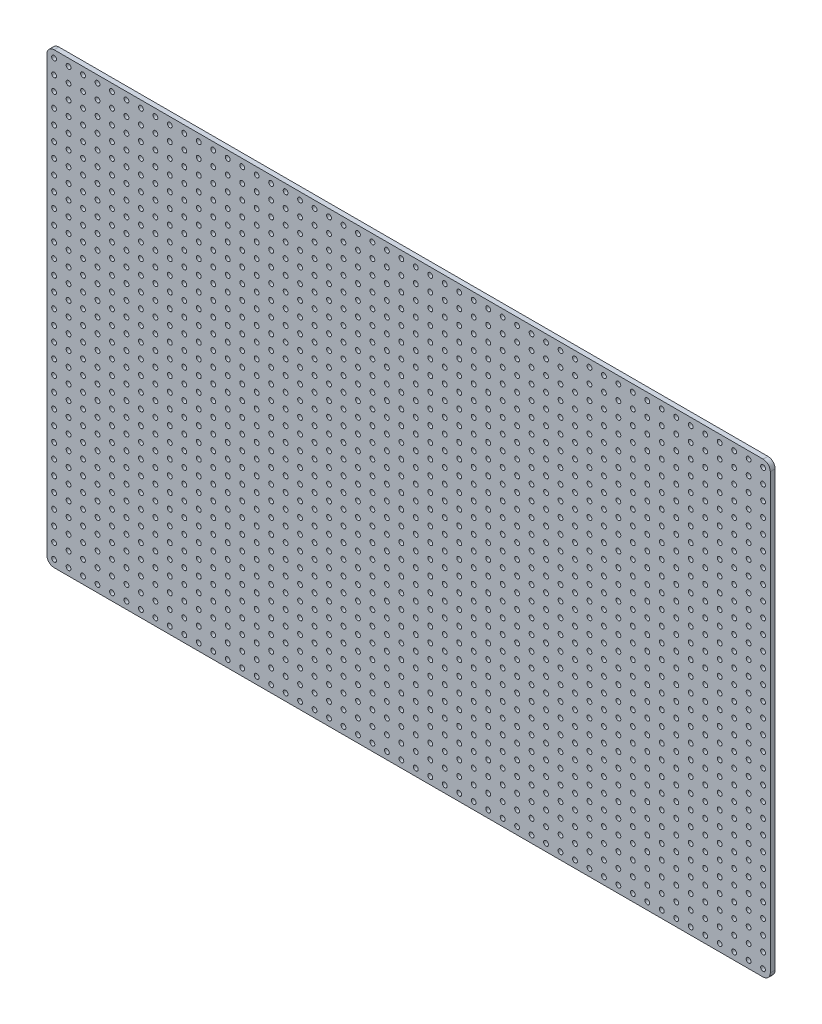
SolidWorks part; units mm, degrees
ref_plane "Alzado" through (0, 0, 0) normal (0, 0, 1) x (1, 0, 0)
ref_plane "Planta" through (0, 0, 0) normal (0, 1, 0) x (1, 0, 0)
ref_plane "Vista lateral" through (0, 0, 0) normal (1, 0, 0) x (0, 0, -1)
sketch "Model" plane through (0, 0, 0) normal (0, 0, 1) x (1, 0, 0)
  line L0 (256.4291, 489.7422) -> (697.4291, 489.7422)
  line L1 (256.4291, 210.7422) -> (697.4291, 210.7422)
  line L2 (251.9291, 215.2422) -> (251.9291, 485.2422)
  line L3 (701.9291, 485.2422) -> (701.9291, 215.2422)
  arc A0 (701.9291, 485.2422) -> (697.4291, 489.7422) centre (697.4291, 485.2422) ccw
  arc A1 (256.4291, 489.7422) -> (251.9291, 485.2422) centre (256.4291, 485.2422) ccw
  arc A2 (697.4291, 210.7422) -> (701.9291, 215.2422) centre (697.4291, 215.2422) ccw
  arc A3 (251.9291, 215.2422) -> (256.4291, 210.7422) centre (256.4291, 215.2422) ccw
  circle A4 centre (256.4291, 485.2422) radius 1.5
  circle A5 centre (256.4291, 476.2422) radius 1.5
  circle A6 centre (256.4291, 467.2422) radius 1.5
  circle A7 centre (256.4291, 458.2422) radius 1.5
  circle A8 centre (256.4291, 449.2422) radius 1.5
  circle A9 centre (256.4291, 440.2422) radius 1.5
  circle A10 centre (256.4291, 431.2422) radius 1.5
  circle A11 centre (256.4291, 422.2422) radius 1.5
  circle A12 centre (256.4291, 413.2422) radius 1.5
  circle A13 centre (256.4291, 404.2422) radius 1.5
  circle A14 centre (256.4291, 395.2422) radius 1.5
  circle A15 centre (256.4291, 386.2422) radius 1.5
  circle A16 centre (256.4291, 377.2422) radius 1.5
  circle A17 centre (256.4291, 368.2422) radius 1.5
  circle A18 centre (256.4291, 359.2422) radius 1.5
  circle A19 centre (256.4291, 350.2422) radius 1.5
  circle A20 centre (256.4291, 341.2422) radius 1.5
  circle A21 centre (256.4291, 332.2422) radius 1.5
  circle A22 centre (256.4291, 323.2422) radius 1.5
  circle A23 centre (256.4291, 314.2422) radius 1.5
  circle A24 centre (256.4291, 305.2422) radius 1.5
  circle A25 centre (265.4291, 485.2422) radius 1.5
  circle A26 centre (265.4291, 476.2422) radius 1.5
  circle A27 centre (265.4291, 467.2422) radius 1.5
  circle A28 centre (265.4291, 458.2422) radius 1.5
  circle A29 centre (265.4291, 449.2422) radius 1.5
  circle A30 centre (265.4291, 440.2422) radius 1.5
  circle A31 centre (265.4291, 431.2422) radius 1.5
  circle A32 centre (265.4291, 422.2422) radius 1.5
  circle A33 centre (265.4291, 413.2422) radius 1.5
  circle A34 centre (265.4291, 404.2422) radius 1.5
  circle A35 centre (265.4291, 395.2422) radius 1.5
  circle A36 centre (265.4291, 386.2422) radius 1.5
  circle A37 centre (265.4291, 377.2422) radius 1.5
  circle A38 centre (265.4291, 368.2422) radius 1.5
  circle A39 centre (265.4291, 359.2422) radius 1.5
  circle A40 centre (265.4291, 350.2422) radius 1.5
  circle A41 centre (265.4291, 341.2422) radius 1.5
  circle A42 centre (265.4291, 332.2422) radius 1.5
  circle A43 centre (265.4291, 323.2422) radius 1.5
  circle A44 centre (265.4291, 314.2422) radius 1.5
  circle A45 centre (265.4291, 305.2422) radius 1.5
  circle A46 centre (274.4291, 485.2422) radius 1.5
  circle A47 centre (274.4291, 476.2422) radius 1.5
  circle A48 centre (274.4291, 467.2422) radius 1.5
  circle A49 centre (274.4291, 458.2422) radius 1.5
  circle A50 centre (274.4291, 449.2422) radius 1.5
  circle A51 centre (274.4291, 440.2422) radius 1.5
  circle A52 centre (274.4291, 431.2422) radius 1.5
  circle A53 centre (274.4291, 422.2422) radius 1.5
  circle A54 centre (274.4291, 413.2422) radius 1.5
  circle A55 centre (274.4291, 404.2422) radius 1.5
  circle A56 centre (274.4291, 395.2422) radius 1.5
  circle A57 centre (274.4291, 386.2422) radius 1.5
  circle A58 centre (274.4291, 377.2422) radius 1.5
  circle A59 centre (274.4291, 368.2422) radius 1.5
  circle A60 centre (274.4291, 359.2422) radius 1.5
  circle A61 centre (274.4291, 350.2422) radius 1.5
  circle A62 centre (274.4291, 341.2422) radius 1.5
  circle A63 centre (274.4291, 332.2422) radius 1.5
  circle A64 centre (274.4291, 323.2422) radius 1.5
  circle A65 centre (274.4291, 314.2422) radius 1.5
  circle A66 centre (274.4291, 305.2422) radius 1.5
  circle A67 centre (283.4291, 485.2422) radius 1.5
  circle A68 centre (283.4291, 476.2422) radius 1.5
  circle A69 centre (283.4291, 467.2422) radius 1.5
  circle A70 centre (283.4291, 458.2422) radius 1.5
  circle A71 centre (283.4291, 449.2422) radius 1.5
  circle A72 centre (283.4291, 440.2422) radius 1.5
  circle A73 centre (283.4291, 431.2422) radius 1.5
  circle A74 centre (283.4291, 422.2422) radius 1.5
  circle A75 centre (283.4291, 413.2422) radius 1.5
  circle A76 centre (283.4291, 404.2422) radius 1.5
  circle A77 centre (283.4291, 395.2422) radius 1.5
  circle A78 centre (283.4291, 386.2422) radius 1.5
  circle A79 centre (283.4291, 377.2422) radius 1.5
  circle A80 centre (283.4291, 368.2422) radius 1.5
  circle A81 centre (283.4291, 359.2422) radius 1.5
  circle A82 centre (283.4291, 350.2422) radius 1.5
  circle A83 centre (283.4291, 341.2422) radius 1.5
  circle A84 centre (283.4291, 332.2422) radius 1.5
  circle A85 centre (283.4291, 323.2422) radius 1.5
  circle A86 centre (283.4291, 314.2422) radius 1.5
  circle A87 centre (283.4291, 305.2422) radius 1.5
  circle A88 centre (292.4291, 485.2422) radius 1.5
  circle A89 centre (292.4291, 476.2422) radius 1.5
  circle A90 centre (292.4291, 467.2422) radius 1.5
  circle A91 centre (292.4291, 458.2422) radius 1.5
  circle A92 centre (292.4291, 449.2422) radius 1.5
  circle A93 centre (292.4291, 440.2422) radius 1.5
  circle A94 centre (292.4291, 431.2422) radius 1.5
  circle A95 centre (292.4291, 422.2422) radius 1.5
  circle A96 centre (292.4291, 413.2422) radius 1.5
  circle A97 centre (292.4291, 404.2422) radius 1.5
  circle A98 centre (292.4291, 395.2422) radius 1.5
  circle A99 centre (292.4291, 386.2422) radius 1.5
  circle A100 centre (292.4291, 377.2422) radius 1.5
  circle A101 centre (292.4291, 368.2422) radius 1.5
  circle A102 centre (292.4291, 359.2422) radius 1.5
  circle A103 centre (292.4291, 350.2422) radius 1.5
  circle A104 centre (292.4291, 341.2422) radius 1.5
  circle A105 centre (292.4291, 332.2422) radius 1.5
  circle A106 centre (292.4291, 323.2422) radius 1.5
  circle A107 centre (292.4291, 314.2422) radius 1.5
  circle A108 centre (292.4291, 305.2422) radius 1.5
  circle A109 centre (301.4291, 485.2422) radius 1.5
  circle A110 centre (301.4291, 476.2422) radius 1.5
  circle A111 centre (301.4291, 467.2422) radius 1.5
  circle A112 centre (301.4291, 458.2422) radius 1.5
  circle A113 centre (301.4291, 449.2422) radius 1.5
  circle A114 centre (301.4291, 440.2422) radius 1.5
  circle A115 centre (301.4291, 431.2422) radius 1.5
  circle A116 centre (301.4291, 422.2422) radius 1.5
  circle A117 centre (301.4291, 413.2422) radius 1.5
  circle A118 centre (301.4291, 404.2422) radius 1.5
  circle A119 centre (301.4291, 395.2422) radius 1.5
  circle A120 centre (301.4291, 386.2422) radius 1.5
  circle A121 centre (301.4291, 377.2422) radius 1.5
  circle A122 centre (301.4291, 368.2422) radius 1.5
  circle A123 centre (301.4291, 359.2422) radius 1.5
  circle A124 centre (301.4291, 350.2422) radius 1.5
  circle A125 centre (301.4291, 341.2422) radius 1.5
  circle A126 centre (301.4291, 332.2422) radius 1.5
  circle A127 centre (301.4291, 323.2422) radius 1.5
  circle A128 centre (301.4291, 314.2422) radius 1.5
  circle A129 centre (301.4291, 305.2422) radius 1.5
  circle A130 centre (310.4291, 485.2422) radius 1.5
  circle A131 centre (310.4291, 476.2422) radius 1.5
  circle A132 centre (310.4291, 467.2422) radius 1.5
  circle A133 centre (310.4291, 458.2422) radius 1.5
  circle A134 centre (310.4291, 449.2422) radius 1.5
  circle A135 centre (310.4291, 440.2422) radius 1.5
  circle A136 centre (310.4291, 431.2422) radius 1.5
  circle A137 centre (310.4291, 422.2422) radius 1.5
  circle A138 centre (310.4291, 413.2422) radius 1.5
  circle A139 centre (310.4291, 404.2422) radius 1.5
  circle A140 centre (310.4291, 395.2422) radius 1.5
  circle A141 centre (310.4291, 386.2422) radius 1.5
  circle A142 centre (310.4291, 377.2422) radius 1.5
  circle A143 centre (310.4291, 368.2422) radius 1.5
  circle A144 centre (310.4291, 359.2422) radius 1.5
  circle A145 centre (310.4291, 350.2422) radius 1.5
  circle A146 centre (310.4291, 341.2422) radius 1.5
  circle A147 centre (310.4291, 332.2422) radius 1.5
  circle A148 centre (310.4291, 323.2422) radius 1.5
  circle A149 centre (310.4291, 314.2422) radius 1.5
  circle A150 centre (310.4291, 305.2422) radius 1.5
  circle A151 centre (319.4291, 485.2422) radius 1.5
  circle A152 centre (319.4291, 476.2422) radius 1.5
  circle A153 centre (319.4291, 467.2422) radius 1.5
  circle A154 centre (319.4291, 458.2422) radius 1.5
  circle A155 centre (319.4291, 449.2422) radius 1.5
  circle A156 centre (319.4291, 440.2422) radius 1.5
  circle A157 centre (319.4291, 431.2422) radius 1.5
  circle A158 centre (319.4291, 422.2422) radius 1.5
  circle A159 centre (319.4291, 413.2422) radius 1.5
  circle A160 centre (319.4291, 404.2422) radius 1.5
  circle A161 centre (319.4291, 395.2422) radius 1.5
  circle A162 centre (319.4291, 386.2422) radius 1.5
  circle A163 centre (319.4291, 377.2422) radius 1.5
  circle A164 centre (319.4291, 368.2422) radius 1.5
  circle A165 centre (319.4291, 359.2422) radius 1.5
  circle A166 centre (319.4291, 350.2422) radius 1.5
  circle A167 centre (319.4291, 341.2422) radius 1.5
  circle A168 centre (319.4291, 332.2422) radius 1.5
  circle A169 centre (319.4291, 323.2422) radius 1.5
  circle A170 centre (319.4291, 314.2422) radius 1.5
  circle A171 centre (319.4291, 305.2422) radius 1.5
  circle A172 centre (328.4291, 485.2422) radius 1.5
  circle A173 centre (328.4291, 476.2422) radius 1.5
  circle A174 centre (328.4291, 467.2422) radius 1.5
  circle A175 centre (328.4291, 458.2422) radius 1.5
  circle A176 centre (328.4291, 449.2422) radius 1.5
  circle A177 centre (328.4291, 440.2422) radius 1.5
  circle A178 centre (328.4291, 431.2422) radius 1.5
  circle A179 centre (328.4291, 422.2422) radius 1.5
  circle A180 centre (328.4291, 413.2422) radius 1.5
  circle A181 centre (328.4291, 404.2422) radius 1.5
  circle A182 centre (328.4291, 395.2422) radius 1.5
  circle A183 centre (328.4291, 386.2422) radius 1.5
  circle A184 centre (328.4291, 377.2422) radius 1.5
  circle A185 centre (328.4291, 368.2422) radius 1.5
  circle A186 centre (328.4291, 359.2422) radius 1.5
  circle A187 centre (328.4291, 350.2422) radius 1.5
  circle A188 centre (328.4291, 341.2422) radius 1.5
  circle A189 centre (328.4291, 332.2422) radius 1.5
  circle A190 centre (328.4291, 323.2422) radius 1.5
  circle A191 centre (328.4291, 314.2422) radius 1.5
  circle A192 centre (328.4291, 305.2422) radius 1.5
  circle A193 centre (337.4291, 485.2422) radius 1.5
  circle A194 centre (337.4291, 476.2422) radius 1.5
  circle A195 centre (337.4291, 467.2422) radius 1.5
  circle A196 centre (337.4291, 458.2422) radius 1.5
  circle A197 centre (337.4291, 449.2422) radius 1.5
  circle A198 centre (337.4291, 440.2422) radius 1.5
  circle A199 centre (337.4291, 431.2422) radius 1.5
  circle A200 centre (337.4291, 422.2422) radius 1.5
  circle A201 centre (337.4291, 413.2422) radius 1.5
  circle A202 centre (337.4291, 404.2422) radius 1.5
  circle A203 centre (337.4291, 395.2422) radius 1.5
  circle A204 centre (337.4291, 386.2422) radius 1.5
  circle A205 centre (337.4291, 377.2422) radius 1.5
  circle A206 centre (337.4291, 368.2422) radius 1.5
  circle A207 centre (337.4291, 359.2422) radius 1.5
  circle A208 centre (337.4291, 350.2422) radius 1.5
  circle A209 centre (337.4291, 341.2422) radius 1.5
  circle A210 centre (337.4291, 332.2422) radius 1.5
  circle A211 centre (337.4291, 323.2422) radius 1.5
  circle A212 centre (337.4291, 314.2422) radius 1.5
  circle A213 centre (337.4291, 305.2422) radius 1.5
  circle A214 centre (346.4291, 485.2422) radius 1.5
  circle A215 centre (346.4291, 476.2422) radius 1.5
  circle A216 centre (346.4291, 467.2422) radius 1.5
  circle A217 centre (346.4291, 458.2422) radius 1.5
  circle A218 centre (346.4291, 449.2422) radius 1.5
  circle A219 centre (346.4291, 440.2422) radius 1.5
  circle A220 centre (346.4291, 431.2422) radius 1.5
  circle A221 centre (346.4291, 422.2422) radius 1.5
  circle A222 centre (346.4291, 413.2422) radius 1.5
  circle A223 centre (346.4291, 404.2422) radius 1.5
  circle A224 centre (346.4291, 395.2422) radius 1.5
  circle A225 centre (346.4291, 386.2422) radius 1.5
  circle A226 centre (346.4291, 377.2422) radius 1.5
  circle A227 centre (346.4291, 368.2422) radius 1.5
  circle A228 centre (346.4291, 359.2422) radius 1.5
  circle A229 centre (346.4291, 350.2422) radius 1.5
  circle A230 centre (346.4291, 341.2422) radius 1.5
  circle A231 centre (346.4291, 332.2422) radius 1.5
  circle A232 centre (346.4291, 323.2422) radius 1.5
  circle A233 centre (346.4291, 314.2422) radius 1.5
  circle A234 centre (346.4291, 305.2422) radius 1.5
  circle A235 centre (355.4291, 485.2422) radius 1.5
  circle A236 centre (355.4291, 476.2422) radius 1.5
  circle A237 centre (355.4291, 467.2422) radius 1.5
  circle A238 centre (355.4291, 458.2422) radius 1.5
  circle A239 centre (355.4291, 449.2422) radius 1.5
  circle A240 centre (355.4291, 440.2422) radius 1.5
  circle A241 centre (355.4291, 431.2422) radius 1.5
  circle A242 centre (355.4291, 422.2422) radius 1.5
  circle A243 centre (355.4291, 413.2422) radius 1.5
  circle A244 centre (355.4291, 404.2422) radius 1.5
  circle A245 centre (355.4291, 395.2422) radius 1.5
  circle A246 centre (355.4291, 386.2422) radius 1.5
  circle A247 centre (355.4291, 377.2422) radius 1.5
  circle A248 centre (355.4291, 368.2422) radius 1.5
  circle A249 centre (355.4291, 359.2422) radius 1.5
  circle A250 centre (355.4291, 350.2422) radius 1.5
  circle A251 centre (355.4291, 341.2422) radius 1.5
  circle A252 centre (355.4291, 332.2422) radius 1.5
  circle A253 centre (355.4291, 323.2422) radius 1.5
  circle A254 centre (355.4291, 314.2422) radius 1.5
  circle A255 centre (355.4291, 305.2422) radius 1.5
  circle A256 centre (364.4291, 485.2422) radius 1.5
  circle A257 centre (364.4291, 476.2422) radius 1.5
  circle A258 centre (364.4291, 467.2422) radius 1.5
  circle A259 centre (364.4291, 458.2422) radius 1.5
  circle A260 centre (364.4291, 449.2422) radius 1.5
  circle A261 centre (364.4291, 440.2422) radius 1.5
  circle A262 centre (364.4291, 431.2422) radius 1.5
  circle A263 centre (364.4291, 422.2422) radius 1.5
  circle A264 centre (364.4291, 413.2422) radius 1.5
  circle A265 centre (364.4291, 404.2422) radius 1.5
  circle A266 centre (364.4291, 395.2422) radius 1.5
  circle A267 centre (364.4291, 386.2422) radius 1.5
  circle A268 centre (364.4291, 377.2422) radius 1.5
  circle A269 centre (364.4291, 368.2422) radius 1.5
  circle A270 centre (364.4291, 359.2422) radius 1.5
  circle A271 centre (364.4291, 350.2422) radius 1.5
  circle A272 centre (364.4291, 341.2422) radius 1.5
  circle A273 centre (364.4291, 332.2422) radius 1.5
  circle A274 centre (364.4291, 323.2422) radius 1.5
  circle A275 centre (364.4291, 314.2422) radius 1.5
  circle A276 centre (364.4291, 305.2422) radius 1.5
  circle A277 centre (373.4291, 485.2422) radius 1.5
  circle A278 centre (373.4291, 476.2422) radius 1.5
  circle A279 centre (373.4291, 467.2422) radius 1.5
  circle A280 centre (373.4291, 458.2422) radius 1.5
  circle A281 centre (373.4291, 449.2422) radius 1.5
  circle A282 centre (373.4291, 440.2422) radius 1.5
  circle A283 centre (373.4291, 431.2422) radius 1.5
  circle A284 centre (373.4291, 422.2422) radius 1.5
  circle A285 centre (373.4291, 413.2422) radius 1.5
  circle A286 centre (373.4291, 404.2422) radius 1.5
  circle A287 centre (373.4291, 395.2422) radius 1.5
  circle A288 centre (373.4291, 386.2422) radius 1.5
  circle A289 centre (373.4291, 377.2422) radius 1.5
  circle A290 centre (373.4291, 368.2422) radius 1.5
  circle A291 centre (373.4291, 359.2422) radius 1.5
  circle A292 centre (373.4291, 350.2422) radius 1.5
  circle A293 centre (373.4291, 341.2422) radius 1.5
  circle A294 centre (373.4291, 332.2422) radius 1.5
  circle A295 centre (373.4291, 323.2422) radius 1.5
  circle A296 centre (373.4291, 314.2422) radius 1.5
  circle A297 centre (373.4291, 305.2422) radius 1.5
  circle A298 centre (382.4291, 485.2422) radius 1.5
  circle A299 centre (382.4291, 476.2422) radius 1.5
  circle A300 centre (382.4291, 467.2422) radius 1.5
  circle A301 centre (382.4291, 458.2422) radius 1.5
  circle A302 centre (382.4291, 449.2422) radius 1.5
  circle A303 centre (382.4291, 440.2422) radius 1.5
  circle A304 centre (382.4291, 431.2422) radius 1.5
  circle A305 centre (382.4291, 422.2422) radius 1.5
  circle A306 centre (382.4291, 413.2422) radius 1.5
  circle A307 centre (382.4291, 404.2422) radius 1.5
  circle A308 centre (382.4291, 395.2422) radius 1.5
  circle A309 centre (382.4291, 386.2422) radius 1.5
  circle A310 centre (382.4291, 377.2422) radius 1.5
  circle A311 centre (382.4291, 368.2422) radius 1.5
  circle A312 centre (382.4291, 359.2422) radius 1.5
  circle A313 centre (382.4291, 350.2422) radius 1.5
  circle A314 centre (382.4291, 341.2422) radius 1.5
  circle A315 centre (382.4291, 332.2422) radius 1.5
  circle A316 centre (382.4291, 323.2422) radius 1.5
  circle A317 centre (382.4291, 314.2422) radius 1.5
  circle A318 centre (382.4291, 305.2422) radius 1.5
  circle A319 centre (391.4291, 485.2422) radius 1.5
  circle A320 centre (391.4291, 476.2422) radius 1.5
  circle A321 centre (391.4291, 467.2422) radius 1.5
  circle A322 centre (391.4291, 458.2422) radius 1.5
  circle A323 centre (391.4291, 449.2422) radius 1.5
  circle A324 centre (391.4291, 440.2422) radius 1.5
  circle A325 centre (391.4291, 431.2422) radius 1.5
  circle A326 centre (391.4291, 422.2422) radius 1.5
  circle A327 centre (391.4291, 413.2422) radius 1.5
  circle A328 centre (391.4291, 404.2422) radius 1.5
  circle A329 centre (391.4291, 395.2422) radius 1.5
  circle A330 centre (391.4291, 386.2422) radius 1.5
  circle A331 centre (391.4291, 377.2422) radius 1.5
  circle A332 centre (391.4291, 368.2422) radius 1.5
  circle A333 centre (391.4291, 359.2422) radius 1.5
  circle A334 centre (391.4291, 350.2422) radius 1.5
  circle A335 centre (391.4291, 341.2422) radius 1.5
  circle A336 centre (391.4291, 332.2422) radius 1.5
  circle A337 centre (391.4291, 323.2422) radius 1.5
  circle A338 centre (391.4291, 314.2422) radius 1.5
  circle A339 centre (391.4291, 305.2422) radius 1.5
  circle A340 centre (400.4291, 485.2422) radius 1.5
  circle A341 centre (400.4291, 476.2422) radius 1.5
  circle A342 centre (400.4291, 467.2422) radius 1.5
  circle A343 centre (400.4291, 458.2422) radius 1.5
  circle A344 centre (400.4291, 449.2422) radius 1.5
  circle A345 centre (400.4291, 440.2422) radius 1.5
  circle A346 centre (400.4291, 431.2422) radius 1.5
  circle A347 centre (400.4291, 422.2422) radius 1.5
  circle A348 centre (400.4291, 413.2422) radius 1.5
  circle A349 centre (400.4291, 404.2422) radius 1.5
  circle A350 centre (400.4291, 395.2422) radius 1.5
  circle A351 centre (400.4291, 386.2422) radius 1.5
  circle A352 centre (400.4291, 377.2422) radius 1.5
  circle A353 centre (400.4291, 368.2422) radius 1.5
  circle A354 centre (400.4291, 359.2422) radius 1.5
  circle A355 centre (400.4291, 350.2422) radius 1.5
  circle A356 centre (400.4291, 341.2422) radius 1.5
  circle A357 centre (400.4291, 332.2422) radius 1.5
  circle A358 centre (400.4291, 323.2422) radius 1.5
  circle A359 centre (400.4291, 314.2422) radius 1.5
  circle A360 centre (400.4291, 305.2422) radius 1.5
  circle A361 centre (409.4291, 485.2422) radius 1.5
  circle A362 centre (409.4291, 476.2422) radius 1.5
  circle A363 centre (409.4291, 467.2422) radius 1.5
  circle A364 centre (409.4291, 458.2422) radius 1.5
  circle A365 centre (409.4291, 449.2422) radius 1.5
  circle A366 centre (409.4291, 440.2422) radius 1.5
  circle A367 centre (409.4291, 431.2422) radius 1.5
  circle A368 centre (409.4291, 422.2422) radius 1.5
  circle A369 centre (409.4291, 413.2422) radius 1.5
  circle A370 centre (409.4291, 404.2422) radius 1.5
  circle A371 centre (409.4291, 395.2422) radius 1.5
  circle A372 centre (409.4291, 386.2422) radius 1.5
  circle A373 centre (409.4291, 377.2422) radius 1.5
  circle A374 centre (409.4291, 368.2422) radius 1.5
  circle A375 centre (409.4291, 359.2422) radius 1.5
  circle A376 centre (409.4291, 350.2422) radius 1.5
  circle A377 centre (409.4291, 341.2422) radius 1.5
  circle A378 centre (409.4291, 332.2422) radius 1.5
  circle A379 centre (409.4291, 323.2422) radius 1.5
  circle A380 centre (409.4291, 314.2422) radius 1.5
  circle A381 centre (409.4291, 305.2422) radius 1.5
  circle A382 centre (418.4291, 485.2422) radius 1.5
  circle A383 centre (418.4291, 476.2422) radius 1.5
  circle A384 centre (418.4291, 467.2422) radius 1.5
  circle A385 centre (418.4291, 458.2422) radius 1.5
  circle A386 centre (418.4291, 449.2422) radius 1.5
  circle A387 centre (418.4291, 440.2422) radius 1.5
  circle A388 centre (418.4291, 431.2422) radius 1.5
  circle A389 centre (418.4291, 422.2422) radius 1.5
  circle A390 centre (418.4291, 413.2422) radius 1.5
  circle A391 centre (418.4291, 404.2422) radius 1.5
  circle A392 centre (418.4291, 395.2422) radius 1.5
  circle A393 centre (418.4291, 386.2422) radius 1.5
  circle A394 centre (418.4291, 377.2422) radius 1.5
  circle A395 centre (418.4291, 368.2422) radius 1.5
  circle A396 centre (418.4291, 359.2422) radius 1.5
  circle A397 centre (418.4291, 350.2422) radius 1.5
  circle A398 centre (418.4291, 341.2422) radius 1.5
  circle A399 centre (418.4291, 332.2422) radius 1.5
  circle A400 centre (418.4291, 323.2422) radius 1.5
  circle A401 centre (418.4291, 314.2422) radius 1.5
  circle A402 centre (418.4291, 305.2422) radius 1.5
  circle A403 centre (427.4291, 485.2422) radius 1.5
  circle A404 centre (427.4291, 476.2422) radius 1.5
  circle A405 centre (427.4291, 467.2422) radius 1.5
  circle A406 centre (427.4291, 458.2422) radius 1.5
  circle A407 centre (427.4291, 449.2422) radius 1.5
  circle A408 centre (427.4291, 440.2422) radius 1.5
  circle A409 centre (427.4291, 431.2422) radius 1.5
  circle A410 centre (427.4291, 422.2422) radius 1.5
  circle A411 centre (427.4291, 413.2422) radius 1.5
  circle A412 centre (427.4291, 404.2422) radius 1.5
  circle A413 centre (427.4291, 395.2422) radius 1.5
  circle A414 centre (427.4291, 386.2422) radius 1.5
  circle A415 centre (427.4291, 377.2422) radius 1.5
  circle A416 centre (427.4291, 368.2422) radius 1.5
  circle A417 centre (427.4291, 359.2422) radius 1.5
  circle A418 centre (427.4291, 350.2422) radius 1.5
  circle A419 centre (427.4291, 341.2422) radius 1.5
  circle A420 centre (427.4291, 332.2422) radius 1.5
  circle A421 centre (427.4291, 323.2422) radius 1.5
  circle A422 centre (427.4291, 314.2422) radius 1.5
  circle A423 centre (427.4291, 305.2422) radius 1.5
  circle A424 centre (436.4291, 485.2422) radius 1.5
  circle A425 centre (436.4291, 476.2422) radius 1.5
  circle A426 centre (436.4291, 467.2422) radius 1.5
  circle A427 centre (436.4291, 458.2422) radius 1.5
  circle A428 centre (436.4291, 449.2422) radius 1.5
  circle A429 centre (436.4291, 440.2422) radius 1.5
  circle A430 centre (436.4291, 431.2422) radius 1.5
  circle A431 centre (436.4291, 422.2422) radius 1.5
  circle A432 centre (436.4291, 413.2422) radius 1.5
  circle A433 centre (436.4291, 404.2422) radius 1.5
  circle A434 centre (436.4291, 395.2422) radius 1.5
  circle A435 centre (436.4291, 386.2422) radius 1.5
  circle A436 centre (436.4291, 377.2422) radius 1.5
  circle A437 centre (436.4291, 368.2422) radius 1.5
  circle A438 centre (436.4291, 359.2422) radius 1.5
  circle A439 centre (436.4291, 350.2422) radius 1.5
  circle A440 centre (436.4291, 341.2422) radius 1.5
  circle A441 centre (436.4291, 332.2422) radius 1.5
  circle A442 centre (436.4291, 323.2422) radius 1.5
  circle A443 centre (436.4291, 314.2422) radius 1.5
  circle A444 centre (436.4291, 305.2422) radius 1.5
  circle A445 centre (445.4291, 485.2422) radius 1.5
  circle A446 centre (445.4291, 476.2422) radius 1.5
  circle A447 centre (445.4291, 467.2422) radius 1.5
  circle A448 centre (445.4291, 458.2422) radius 1.5
  circle A449 centre (445.4291, 449.2422) radius 1.5
  circle A450 centre (445.4291, 440.2422) radius 1.5
  circle A451 centre (445.4291, 431.2422) radius 1.5
  circle A452 centre (445.4291, 422.2422) radius 1.5
  circle A453 centre (445.4291, 413.2422) radius 1.5
  circle A454 centre (445.4291, 404.2422) radius 1.5
  circle A455 centre (445.4291, 395.2422) radius 1.5
  circle A456 centre (445.4291, 386.2422) radius 1.5
  circle A457 centre (445.4291, 377.2422) radius 1.5
  circle A458 centre (445.4291, 368.2422) radius 1.5
  circle A459 centre (445.4291, 359.2422) radius 1.5
  circle A460 centre (445.4291, 350.2422) radius 1.5
  circle A461 centre (445.4291, 341.2422) radius 1.5
  circle A462 centre (445.4291, 332.2422) radius 1.5
  circle A463 centre (445.4291, 323.2422) radius 1.5
  circle A464 centre (445.4291, 314.2422) radius 1.5
  circle A465 centre (445.4291, 305.2422) radius 1.5
  circle A466 centre (454.4291, 485.2422) radius 1.5
  circle A467 centre (454.4291, 476.2422) radius 1.5
  circle A468 centre (454.4291, 467.2422) radius 1.5
  circle A469 centre (454.4291, 458.2422) radius 1.5
  circle A470 centre (454.4291, 449.2422) radius 1.5
  circle A471 centre (454.4291, 440.2422) radius 1.5
  circle A472 centre (454.4291, 431.2422) radius 1.5
  circle A473 centre (454.4291, 422.2422) radius 1.5
  circle A474 centre (454.4291, 413.2422) radius 1.5
  circle A475 centre (454.4291, 404.2422) radius 1.5
  circle A476 centre (454.4291, 395.2422) radius 1.5
  circle A477 centre (454.4291, 386.2422) radius 1.5
  circle A478 centre (454.4291, 377.2422) radius 1.5
  circle A479 centre (454.4291, 368.2422) radius 1.5
  circle A480 centre (454.4291, 359.2422) radius 1.5
  circle A481 centre (454.4291, 350.2422) radius 1.5
  circle A482 centre (454.4291, 341.2422) radius 1.5
  circle A483 centre (454.4291, 332.2422) radius 1.5
  circle A484 centre (454.4291, 323.2422) radius 1.5
  circle A485 centre (454.4291, 314.2422) radius 1.5
  circle A486 centre (454.4291, 305.2422) radius 1.5
  circle A487 centre (463.4291, 485.2422) radius 1.5
  circle A488 centre (463.4291, 476.2422) radius 1.5
  circle A489 centre (463.4291, 467.2422) radius 1.5
  circle A490 centre (463.4291, 458.2422) radius 1.5
  circle A491 centre (463.4291, 449.2422) radius 1.5
  circle A492 centre (463.4291, 440.2422) radius 1.5
  circle A493 centre (463.4291, 431.2422) radius 1.5
  circle A494 centre (463.4291, 422.2422) radius 1.5
  circle A495 centre (463.4291, 413.2422) radius 1.5
  circle A496 centre (463.4291, 404.2422) radius 1.5
  circle A497 centre (463.4291, 395.2422) radius 1.5
  circle A498 centre (463.4291, 386.2422) radius 1.5
  circle A499 centre (463.4291, 377.2422) radius 1.5
  circle A500 centre (463.4291, 368.2422) radius 1.5
  circle A501 centre (463.4291, 359.2422) radius 1.5
  circle A502 centre (463.4291, 350.2422) radius 1.5
  circle A503 centre (463.4291, 341.2422) radius 1.5
  circle A504 centre (463.4291, 332.2422) radius 1.5
  circle A505 centre (463.4291, 323.2422) radius 1.5
  circle A506 centre (463.4291, 314.2422) radius 1.5
  circle A507 centre (463.4291, 305.2422) radius 1.5
  circle A508 centre (472.4291, 485.2422) radius 1.5
  circle A509 centre (472.4291, 476.2422) radius 1.5
  circle A510 centre (472.4291, 467.2422) radius 1.5
  circle A511 centre (472.4291, 458.2422) radius 1.5
  circle A512 centre (472.4291, 449.2422) radius 1.5
  circle A513 centre (472.4291, 440.2422) radius 1.5
  circle A514 centre (472.4291, 431.2422) radius 1.5
  circle A515 centre (472.4291, 422.2422) radius 1.5
  circle A516 centre (472.4291, 413.2422) radius 1.5
  circle A517 centre (472.4291, 404.2422) radius 1.5
  circle A518 centre (472.4291, 395.2422) radius 1.5
  circle A519 centre (472.4291, 386.2422) radius 1.5
  circle A520 centre (472.4291, 377.2422) radius 1.5
  circle A521 centre (472.4291, 368.2422) radius 1.5
  circle A522 centre (472.4291, 359.2422) radius 1.5
  circle A523 centre (472.4291, 350.2422) radius 1.5
  circle A524 centre (472.4291, 341.2422) radius 1.5
  circle A525 centre (472.4291, 332.2422) radius 1.5
  circle A526 centre (472.4291, 323.2422) radius 1.5
  circle A527 centre (472.4291, 314.2422) radius 1.5
  circle A528 centre (472.4291, 305.2422) radius 1.5
  circle A529 centre (481.4291, 485.2422) radius 1.5
  circle A530 centre (481.4291, 476.2422) radius 1.5
  circle A531 centre (481.4291, 467.2422) radius 1.5
  circle A532 centre (481.4291, 458.2422) radius 1.5
  circle A533 centre (481.4291, 449.2422) radius 1.5
  circle A534 centre (481.4291, 440.2422) radius 1.5
  circle A535 centre (481.4291, 431.2422) radius 1.5
  circle A536 centre (481.4291, 422.2422) radius 1.5
  circle A537 centre (481.4291, 413.2422) radius 1.5
  circle A538 centre (481.4291, 404.2422) radius 1.5
  circle A539 centre (481.4291, 395.2422) radius 1.5
  circle A540 centre (481.4291, 386.2422) radius 1.5
  circle A541 centre (481.4291, 377.2422) radius 1.5
  circle A542 centre (481.4291, 368.2422) radius 1.5
  circle A543 centre (481.4291, 359.2422) radius 1.5
  circle A544 centre (481.4291, 350.2422) radius 1.5
  circle A545 centre (481.4291, 341.2422) radius 1.5
  circle A546 centre (481.4291, 332.2422) radius 1.5
  circle A547 centre (481.4291, 323.2422) radius 1.5
  circle A548 centre (481.4291, 314.2422) radius 1.5
  circle A549 centre (481.4291, 305.2422) radius 1.5
  circle A550 centre (490.4291, 485.2422) radius 1.5
  circle A551 centre (490.4291, 476.2422) radius 1.5
  circle A552 centre (490.4291, 467.2422) radius 1.5
  circle A553 centre (490.4291, 458.2422) radius 1.5
  circle A554 centre (490.4291, 449.2422) radius 1.5
  circle A555 centre (490.4291, 440.2422) radius 1.5
  circle A556 centre (490.4291, 431.2422) radius 1.5
  circle A557 centre (490.4291, 422.2422) radius 1.5
  circle A558 centre (490.4291, 413.2422) radius 1.5
  circle A559 centre (490.4291, 404.2422) radius 1.5
  circle A560 centre (490.4291, 395.2422) radius 1.5
  circle A561 centre (490.4291, 386.2422) radius 1.5
  circle A562 centre (490.4291, 377.2422) radius 1.5
  circle A563 centre (490.4291, 368.2422) radius 1.5
  circle A564 centre (490.4291, 359.2422) radius 1.5
  circle A565 centre (490.4291, 350.2422) radius 1.5
  circle A566 centre (490.4291, 341.2422) radius 1.5
  circle A567 centre (490.4291, 332.2422) radius 1.5
  circle A568 centre (490.4291, 323.2422) radius 1.5
  circle A569 centre (490.4291, 314.2422) radius 1.5
  circle A570 centre (490.4291, 305.2422) radius 1.5
  circle A571 centre (499.4291, 485.2422) radius 1.5
  circle A572 centre (499.4291, 476.2422) radius 1.5
  circle A573 centre (499.4291, 467.2422) radius 1.5
  circle A574 centre (499.4291, 458.2422) radius 1.5
  circle A575 centre (499.4291, 449.2422) radius 1.5
  circle A576 centre (499.4291, 440.2422) radius 1.5
  circle A577 centre (499.4291, 431.2422) radius 1.5
  circle A578 centre (499.4291, 422.2422) radius 1.5
  circle A579 centre (499.4291, 413.2422) radius 1.5
  circle A580 centre (499.4291, 404.2422) radius 1.5
  circle A581 centre (499.4291, 395.2422) radius 1.5
  circle A582 centre (499.4291, 386.2422) radius 1.5
  circle A583 centre (499.4291, 377.2422) radius 1.5
  circle A584 centre (499.4291, 368.2422) radius 1.5
  circle A585 centre (499.4291, 359.2422) radius 1.5
  circle A586 centre (499.4291, 350.2422) radius 1.5
  circle A587 centre (499.4291, 341.2422) radius 1.5
  circle A588 centre (499.4291, 332.2422) radius 1.5
  circle A589 centre (499.4291, 323.2422) radius 1.5
  circle A590 centre (499.4291, 314.2422) radius 1.5
  circle A591 centre (499.4291, 305.2422) radius 1.5
  circle A592 centre (508.4291, 485.2422) radius 1.5
  circle A593 centre (508.4291, 476.2422) radius 1.5
  circle A594 centre (508.4291, 467.2422) radius 1.5
  circle A595 centre (508.4291, 458.2422) radius 1.5
  circle A596 centre (508.4291, 449.2422) radius 1.5
  circle A597 centre (508.4291, 440.2422) radius 1.5
  circle A598 centre (508.4291, 431.2422) radius 1.5
  circle A599 centre (508.4291, 422.2422) radius 1.5
  circle A600 centre (508.4291, 413.2422) radius 1.5
  circle A601 centre (508.4291, 404.2422) radius 1.5
  circle A602 centre (508.4291, 395.2422) radius 1.5
  circle A603 centre (508.4291, 386.2422) radius 1.5
  circle A604 centre (508.4291, 377.2422) radius 1.5
  circle A605 centre (508.4291, 368.2422) radius 1.5
  circle A606 centre (508.4291, 359.2422) radius 1.5
  circle A607 centre (508.4291, 350.2422) radius 1.5
  circle A608 centre (508.4291, 341.2422) radius 1.5
  circle A609 centre (508.4291, 332.2422) radius 1.5
  circle A610 centre (508.4291, 323.2422) radius 1.5
  circle A611 centre (508.4291, 314.2422) radius 1.5
  circle A612 centre (508.4291, 305.2422) radius 1.5
  circle A613 centre (517.4291, 485.2422) radius 1.5
  circle A614 centre (517.4291, 476.2422) radius 1.5
  circle A615 centre (517.4291, 467.2422) radius 1.5
  circle A616 centre (517.4291, 458.2422) radius 1.5
  circle A617 centre (517.4291, 449.2422) radius 1.5
  circle A618 centre (517.4291, 440.2422) radius 1.5
  circle A619 centre (517.4291, 431.2422) radius 1.5
  circle A620 centre (517.4291, 422.2422) radius 1.5
  circle A621 centre (517.4291, 413.2422) radius 1.5
  circle A622 centre (517.4291, 404.2422) radius 1.5
  circle A623 centre (517.4291, 395.2422) radius 1.5
  circle A624 centre (517.4291, 386.2422) radius 1.5
  circle A625 centre (517.4291, 377.2422) radius 1.5
  circle A626 centre (517.4291, 368.2422) radius 1.5
  circle A627 centre (517.4291, 359.2422) radius 1.5
  circle A628 centre (517.4291, 350.2422) radius 1.5
  circle A629 centre (517.4291, 341.2422) radius 1.5
  circle A630 centre (517.4291, 332.2422) radius 1.5
  circle A631 centre (517.4291, 323.2422) radius 1.5
  circle A632 centre (517.4291, 314.2422) radius 1.5
  circle A633 centre (517.4291, 305.2422) radius 1.5
  circle A634 centre (256.4291, 296.2422) radius 1.5
  circle A635 centre (256.4291, 287.2422) radius 1.5
  circle A636 centre (256.4291, 278.2422) radius 1.5
  circle A637 centre (256.4291, 269.2422) radius 1.5
  circle A638 centre (256.4291, 260.2422) radius 1.5
  circle A639 centre (256.4291, 251.2422) radius 1.5
  circle A640 centre (256.4291, 242.2422) radius 1.5
  circle A641 centre (265.4291, 296.2422) radius 1.5
  circle A642 centre (265.4291, 287.2422) radius 1.5
  circle A643 centre (265.4291, 278.2422) radius 1.5
  circle A644 centre (265.4291, 269.2422) radius 1.5
  circle A645 centre (265.4291, 260.2422) radius 1.5
  circle A646 centre (265.4291, 251.2422) radius 1.5
  circle A647 centre (265.4291, 242.2422) radius 1.5
  circle A648 centre (274.4291, 296.2422) radius 1.5
  circle A649 centre (274.4291, 287.2422) radius 1.5
  circle A650 centre (274.4291, 278.2422) radius 1.5
  circle A651 centre (274.4291, 269.2422) radius 1.5
  circle A652 centre (274.4291, 260.2422) radius 1.5
  circle A653 centre (274.4291, 251.2422) radius 1.5
  circle A654 centre (274.4291, 242.2422) radius 1.5
  circle A655 centre (283.4291, 296.2422) radius 1.5
  circle A656 centre (283.4291, 287.2422) radius 1.5
  circle A657 centre (283.4291, 278.2422) radius 1.5
  circle A658 centre (283.4291, 269.2422) radius 1.5
  circle A659 centre (283.4291, 260.2422) radius 1.5
  circle A660 centre (283.4291, 251.2422) radius 1.5
  circle A661 centre (283.4291, 242.2422) radius 1.5
  circle A662 centre (292.4291, 296.2422) radius 1.5
  circle A663 centre (292.4291, 287.2422) radius 1.5
  circle A664 centre (292.4291, 278.2422) radius 1.5
  circle A665 centre (292.4291, 269.2422) radius 1.5
  circle A666 centre (292.4291, 260.2422) radius 1.5
  circle A667 centre (292.4291, 251.2422) radius 1.5
  circle A668 centre (292.4291, 242.2422) radius 1.5
  circle A669 centre (301.4291, 296.2422) radius 1.5
  circle A670 centre (301.4291, 287.2422) radius 1.5
  circle A671 centre (301.4291, 278.2422) radius 1.5
  circle A672 centre (301.4291, 269.2422) radius 1.5
  circle A673 centre (301.4291, 260.2422) radius 1.5
  circle A674 centre (301.4291, 251.2422) radius 1.5
  circle A675 centre (301.4291, 242.2422) radius 1.5
  circle A676 centre (310.4291, 296.2422) radius 1.5
  circle A677 centre (310.4291, 287.2422) radius 1.5
  circle A678 centre (310.4291, 278.2422) radius 1.5
  circle A679 centre (310.4291, 269.2422) radius 1.5
  circle A680 centre (310.4291, 260.2422) radius 1.5
  circle A681 centre (310.4291, 251.2422) radius 1.5
  circle A682 centre (310.4291, 242.2422) radius 1.5
  circle A683 centre (319.4291, 296.2422) radius 1.5
  circle A684 centre (319.4291, 287.2422) radius 1.5
  circle A685 centre (319.4291, 278.2422) radius 1.5
  circle A686 centre (319.4291, 269.2422) radius 1.5
  circle A687 centre (319.4291, 260.2422) radius 1.5
  circle A688 centre (319.4291, 251.2422) radius 1.5
  circle A689 centre (319.4291, 242.2422) radius 1.5
  circle A690 centre (328.4291, 296.2422) radius 1.5
  circle A691 centre (328.4291, 287.2422) radius 1.5
  circle A692 centre (328.4291, 278.2422) radius 1.5
  circle A693 centre (328.4291, 269.2422) radius 1.5
  circle A694 centre (328.4291, 260.2422) radius 1.5
  circle A695 centre (328.4291, 251.2422) radius 1.5
  circle A696 centre (328.4291, 242.2422) radius 1.5
  circle A697 centre (337.4291, 296.2422) radius 1.5
  circle A698 centre (337.4291, 287.2422) radius 1.5
  circle A699 centre (337.4291, 278.2422) radius 1.5
  circle A700 centre (337.4291, 269.2422) radius 1.5
  circle A701 centre (337.4291, 260.2422) radius 1.5
  circle A702 centre (337.4291, 251.2422) radius 1.5
  circle A703 centre (337.4291, 242.2422) radius 1.5
  circle A704 centre (346.4291, 296.2422) radius 1.5
  circle A705 centre (346.4291, 287.2422) radius 1.5
  circle A706 centre (346.4291, 278.2422) radius 1.5
  circle A707 centre (346.4291, 269.2422) radius 1.5
  circle A708 centre (346.4291, 260.2422) radius 1.5
  circle A709 centre (346.4291, 251.2422) radius 1.5
  circle A710 centre (346.4291, 242.2422) radius 1.5
  circle A711 centre (355.4291, 296.2422) radius 1.5
  circle A712 centre (355.4291, 287.2422) radius 1.5
  circle A713 centre (355.4291, 278.2422) radius 1.5
  circle A714 centre (355.4291, 269.2422) radius 1.5
  circle A715 centre (355.4291, 260.2422) radius 1.5
  circle A716 centre (355.4291, 251.2422) radius 1.5
  circle A717 centre (355.4291, 242.2422) radius 1.5
  circle A718 centre (364.4291, 296.2422) radius 1.5
  circle A719 centre (364.4291, 287.2422) radius 1.5
  circle A720 centre (364.4291, 278.2422) radius 1.5
  circle A721 centre (364.4291, 269.2422) radius 1.5
  circle A722 centre (364.4291, 260.2422) radius 1.5
  circle A723 centre (364.4291, 251.2422) radius 1.5
  circle A724 centre (364.4291, 242.2422) radius 1.5
  circle A725 centre (373.4291, 296.2422) radius 1.5
  circle A726 centre (373.4291, 287.2422) radius 1.5
  circle A727 centre (373.4291, 278.2422) radius 1.5
  circle A728 centre (373.4291, 269.2422) radius 1.5
  circle A729 centre (373.4291, 260.2422) radius 1.5
  circle A730 centre (373.4291, 251.2422) radius 1.5
  circle A731 centre (373.4291, 242.2422) radius 1.5
  circle A732 centre (382.4291, 296.2422) radius 1.5
  circle A733 centre (382.4291, 287.2422) radius 1.5
  circle A734 centre (382.4291, 278.2422) radius 1.5
  circle A735 centre (382.4291, 269.2422) radius 1.5
  circle A736 centre (382.4291, 260.2422) radius 1.5
  circle A737 centre (382.4291, 251.2422) radius 1.5
  circle A738 centre (382.4291, 242.2422) radius 1.5
  circle A739 centre (391.4291, 296.2422) radius 1.5
  circle A740 centre (391.4291, 287.2422) radius 1.5
  circle A741 centre (391.4291, 278.2422) radius 1.5
  circle A742 centre (391.4291, 269.2422) radius 1.5
  circle A743 centre (391.4291, 260.2422) radius 1.5
  circle A744 centre (391.4291, 251.2422) radius 1.5
  circle A745 centre (391.4291, 242.2422) radius 1.5
  circle A746 centre (400.4291, 296.2422) radius 1.5
  circle A747 centre (400.4291, 287.2422) radius 1.5
  circle A748 centre (400.4291, 278.2422) radius 1.5
  circle A749 centre (400.4291, 269.2422) radius 1.5
  circle A750 centre (400.4291, 260.2422) radius 1.5
  circle A751 centre (400.4291, 251.2422) radius 1.5
  circle A752 centre (400.4291, 242.2422) radius 1.5
  circle A753 centre (409.4291, 296.2422) radius 1.5
  circle A754 centre (409.4291, 287.2422) radius 1.5
  circle A755 centre (409.4291, 278.2422) radius 1.5
  circle A756 centre (409.4291, 269.2422) radius 1.5
  circle A757 centre (409.4291, 260.2422) radius 1.5
  circle A758 centre (409.4291, 251.2422) radius 1.5
  circle A759 centre (409.4291, 242.2422) radius 1.5
  circle A760 centre (418.4291, 296.2422) radius 1.5
  circle A761 centre (418.4291, 287.2422) radius 1.5
  circle A762 centre (418.4291, 278.2422) radius 1.5
  circle A763 centre (418.4291, 269.2422) radius 1.5
  circle A764 centre (418.4291, 260.2422) radius 1.5
  circle A765 centre (418.4291, 251.2422) radius 1.5
  circle A766 centre (418.4291, 242.2422) radius 1.5
  circle A767 centre (427.4291, 296.2422) radius 1.5
  circle A768 centre (427.4291, 287.2422) radius 1.5
  circle A769 centre (427.4291, 278.2422) radius 1.5
  circle A770 centre (427.4291, 269.2422) radius 1.5
  circle A771 centre (427.4291, 260.2422) radius 1.5
  circle A772 centre (427.4291, 251.2422) radius 1.5
  circle A773 centre (427.4291, 242.2422) radius 1.5
  circle A774 centre (436.4291, 296.2422) radius 1.5
  circle A775 centre (436.4291, 287.2422) radius 1.5
  circle A776 centre (436.4291, 278.2422) radius 1.5
  circle A777 centre (436.4291, 269.2422) radius 1.5
  circle A778 centre (436.4291, 260.2422) radius 1.5
  circle A779 centre (436.4291, 251.2422) radius 1.5
  circle A780 centre (436.4291, 242.2422) radius 1.5
  circle A781 centre (445.4291, 296.2422) radius 1.5
  circle A782 centre (445.4291, 287.2422) radius 1.5
  circle A783 centre (445.4291, 278.2422) radius 1.5
  circle A784 centre (445.4291, 269.2422) radius 1.5
  circle A785 centre (445.4291, 260.2422) radius 1.5
  circle A786 centre (445.4291, 251.2422) radius 1.5
  circle A787 centre (445.4291, 242.2422) radius 1.5
  circle A788 centre (454.4291, 296.2422) radius 1.5
  circle A789 centre (454.4291, 287.2422) radius 1.5
  circle A790 centre (454.4291, 278.2422) radius 1.5
  circle A791 centre (454.4291, 269.2422) radius 1.5
  circle A792 centre (454.4291, 260.2422) radius 1.5
  circle A793 centre (454.4291, 251.2422) radius 1.5
  circle A794 centre (454.4291, 242.2422) radius 1.5
  circle A795 centre (463.4291, 296.2422) radius 1.5
  circle A796 centre (463.4291, 287.2422) radius 1.5
  circle A797 centre (463.4291, 278.2422) radius 1.5
  circle A798 centre (463.4291, 269.2422) radius 1.5
  circle A799 centre (463.4291, 260.2422) radius 1.5
  circle A800 centre (463.4291, 251.2422) radius 1.5
  circle A801 centre (463.4291, 242.2422) radius 1.5
  circle A802 centre (472.4291, 296.2422) radius 1.5
  circle A803 centre (472.4291, 287.2422) radius 1.5
  circle A804 centre (472.4291, 278.2422) radius 1.5
  circle A805 centre (472.4291, 269.2422) radius 1.5
  circle A806 centre (472.4291, 260.2422) radius 1.5
  circle A807 centre (472.4291, 251.2422) radius 1.5
  circle A808 centre (472.4291, 242.2422) radius 1.5
  circle A809 centre (481.4291, 296.2422) radius 1.5
  circle A810 centre (481.4291, 287.2422) radius 1.5
  circle A811 centre (481.4291, 278.2422) radius 1.5
  circle A812 centre (481.4291, 269.2422) radius 1.5
  circle A813 centre (481.4291, 260.2422) radius 1.5
  circle A814 centre (481.4291, 251.2422) radius 1.5
  circle A815 centre (481.4291, 242.2422) radius 1.5
  circle A816 centre (490.4291, 296.2422) radius 1.5
  circle A817 centre (490.4291, 287.2422) radius 1.5
  circle A818 centre (490.4291, 278.2422) radius 1.5
  circle A819 centre (490.4291, 269.2422) radius 1.5
  circle A820 centre (490.4291, 260.2422) radius 1.5
  circle A821 centre (490.4291, 251.2422) radius 1.5
  circle A822 centre (490.4291, 242.2422) radius 1.5
  circle A823 centre (499.4291, 296.2422) radius 1.5
  circle A824 centre (499.4291, 287.2422) radius 1.5
  circle A825 centre (499.4291, 278.2422) radius 1.5
  circle A826 centre (499.4291, 269.2422) radius 1.5
  circle A827 centre (499.4291, 260.2422) radius 1.5
  circle A828 centre (499.4291, 251.2422) radius 1.5
  circle A829 centre (499.4291, 242.2422) radius 1.5
  circle A830 centre (508.4291, 296.2422) radius 1.5
  circle A831 centre (508.4291, 287.2422) radius 1.5
  circle A832 centre (508.4291, 278.2422) radius 1.5
  circle A833 centre (508.4291, 269.2422) radius 1.5
  circle A834 centre (508.4291, 260.2422) radius 1.5
  circle A835 centre (508.4291, 251.2422) radius 1.5
  circle A836 centre (508.4291, 242.2422) radius 1.5
  circle A837 centre (517.4291, 296.2422) radius 1.5
  circle A838 centre (517.4291, 287.2422) radius 1.5
  circle A839 centre (517.4291, 278.2422) radius 1.5
  circle A840 centre (517.4291, 269.2422) radius 1.5
  circle A841 centre (517.4291, 260.2422) radius 1.5
  circle A842 centre (517.4291, 251.2422) radius 1.5
  circle A843 centre (517.4291, 242.2422) radius 1.5
  circle A844 centre (256.4291, 233.2422) radius 1.5
  circle A845 centre (256.4291, 224.2422) radius 1.5
  circle A846 centre (256.4291, 215.2422) radius 1.5
  circle A847 centre (265.4291, 233.2422) radius 1.5
  circle A848 centre (265.4291, 224.2422) radius 1.5
  circle A849 centre (265.4291, 215.2422) radius 1.5
  circle A850 centre (274.4291, 233.2422) radius 1.5
  circle A851 centre (274.4291, 224.2422) radius 1.5
  circle A852 centre (274.4291, 215.2422) radius 1.5
  circle A853 centre (283.4291, 233.2422) radius 1.5
  circle A854 centre (283.4291, 224.2422) radius 1.5
  circle A855 centre (283.4291, 215.2422) radius 1.5
  circle A856 centre (292.4291, 233.2422) radius 1.5
  circle A857 centre (292.4291, 224.2422) radius 1.5
  circle A858 centre (292.4291, 215.2422) radius 1.5
  circle A859 centre (301.4291, 233.2422) radius 1.5
  circle A860 centre (301.4291, 224.2422) radius 1.5
  circle A861 centre (301.4291, 215.2422) radius 1.5
  circle A862 centre (310.4291, 233.2422) radius 1.5
  circle A863 centre (310.4291, 224.2422) radius 1.5
  circle A864 centre (310.4291, 215.2422) radius 1.5
  circle A865 centre (319.4291, 233.2422) radius 1.5
  circle A866 centre (319.4291, 224.2422) radius 1.5
  circle A867 centre (319.4291, 215.2422) radius 1.5
  circle A868 centre (328.4291, 233.2422) radius 1.5
  circle A869 centre (328.4291, 224.2422) radius 1.5
  circle A870 centre (328.4291, 215.2422) radius 1.5
  circle A871 centre (337.4291, 233.2422) radius 1.5
  circle A872 centre (337.4291, 224.2422) radius 1.5
  circle A873 centre (337.4291, 215.2422) radius 1.5
  circle A874 centre (346.4291, 233.2422) radius 1.5
  circle A875 centre (346.4291, 224.2422) radius 1.5
  circle A876 centre (346.4291, 215.2422) radius 1.5
  circle A877 centre (355.4291, 233.2422) radius 1.5
  circle A878 centre (355.4291, 224.2422) radius 1.5
  circle A879 centre (355.4291, 215.2422) radius 1.5
  circle A880 centre (364.4291, 233.2422) radius 1.5
  circle A881 centre (364.4291, 224.2422) radius 1.5
  circle A882 centre (364.4291, 215.2422) radius 1.5
  circle A883 centre (373.4291, 233.2422) radius 1.5
  circle A884 centre (373.4291, 224.2422) radius 1.5
  circle A885 centre (373.4291, 215.2422) radius 1.5
  circle A886 centre (382.4291, 233.2422) radius 1.5
  circle A887 centre (382.4291, 224.2422) radius 1.5
  circle A888 centre (382.4291, 215.2422) radius 1.5
  circle A889 centre (391.4291, 233.2422) radius 1.5
  circle A890 centre (391.4291, 224.2422) radius 1.5
  circle A891 centre (391.4291, 215.2422) radius 1.5
  circle A892 centre (400.4291, 233.2422) radius 1.5
  circle A893 centre (400.4291, 224.2422) radius 1.5
  circle A894 centre (400.4291, 215.2422) radius 1.5
  circle A895 centre (409.4291, 233.2422) radius 1.5
  circle A896 centre (409.4291, 224.2422) radius 1.5
  circle A897 centre (409.4291, 215.2422) radius 1.5
  circle A898 centre (418.4291, 233.2422) radius 1.5
  circle A899 centre (418.4291, 224.2422) radius 1.5
  circle A900 centre (418.4291, 215.2422) radius 1.5
  circle A901 centre (427.4291, 233.2422) radius 1.5
  circle A902 centre (427.4291, 224.2422) radius 1.5
  circle A903 centre (427.4291, 215.2422) radius 1.5
  circle A904 centre (436.4291, 233.2422) radius 1.5
  circle A905 centre (436.4291, 224.2422) radius 1.5
  circle A906 centre (436.4291, 215.2422) radius 1.5
  circle A907 centre (445.4291, 233.2422) radius 1.5
  circle A908 centre (445.4291, 224.2422) radius 1.5
  circle A909 centre (445.4291, 215.2422) radius 1.5
  circle A910 centre (454.4291, 233.2422) radius 1.5
  circle A911 centre (454.4291, 224.2422) radius 1.5
  circle A912 centre (454.4291, 215.2422) radius 1.5
  circle A913 centre (463.4291, 233.2422) radius 1.5
  circle A914 centre (463.4291, 224.2422) radius 1.5
  circle A915 centre (463.4291, 215.2422) radius 1.5
  circle A916 centre (472.4291, 233.2422) radius 1.5
  circle A917 centre (472.4291, 224.2422) radius 1.5
  circle A918 centre (472.4291, 215.2422) radius 1.5
  circle A919 centre (481.4291, 233.2422) radius 1.5
  circle A920 centre (481.4291, 224.2422) radius 1.5
  circle A921 centre (481.4291, 215.2422) radius 1.5
  circle A922 centre (490.4291, 233.2422) radius 1.5
  circle A923 centre (490.4291, 224.2422) radius 1.5
  circle A924 centre (490.4291, 215.2422) radius 1.5
  circle A925 centre (499.4291, 233.2422) radius 1.5
  circle A926 centre (499.4291, 224.2422) radius 1.5
  circle A927 centre (499.4291, 215.2422) radius 1.5
  circle A928 centre (508.4291, 233.2422) radius 1.5
  circle A929 centre (508.4291, 224.2422) radius 1.5
  circle A930 centre (508.4291, 215.2422) radius 1.5
  circle A931 centre (517.4291, 233.2422) radius 1.5
  circle A932 centre (517.4291, 224.2422) radius 1.5
  circle A933 centre (517.4291, 215.2422) radius 1.5
  circle A934 centre (526.4291, 485.2422) radius 1.5
  circle A935 centre (526.4291, 476.2422) radius 1.5
  circle A936 centre (526.4291, 467.2422) radius 1.5
  circle A937 centre (526.4291, 458.2422) radius 1.5
  circle A938 centre (526.4291, 449.2422) radius 1.5
  circle A939 centre (526.4291, 440.2422) radius 1.5
  circle A940 centre (526.4291, 431.2422) radius 1.5
  circle A941 centre (526.4291, 422.2422) radius 1.5
  circle A942 centre (526.4291, 413.2422) radius 1.5
  circle A943 centre (526.4291, 404.2422) radius 1.5
  circle A944 centre (526.4291, 395.2422) radius 1.5
  circle A945 centre (526.4291, 386.2422) radius 1.5
  circle A946 centre (526.4291, 377.2422) radius 1.5
  circle A947 centre (526.4291, 368.2422) radius 1.5
  circle A948 centre (526.4291, 359.2422) radius 1.5
  circle A949 centre (526.4291, 350.2422) radius 1.5
  circle A950 centre (526.4291, 341.2422) radius 1.5
  circle A951 centre (526.4291, 332.2422) radius 1.5
  circle A952 centre (526.4291, 323.2422) radius 1.5
  circle A953 centre (526.4291, 314.2422) radius 1.5
  circle A954 centre (526.4291, 305.2422) radius 1.5
  circle A955 centre (535.4291, 485.2422) radius 1.5
  circle A956 centre (535.4291, 476.2422) radius 1.5
  circle A957 centre (535.4291, 467.2422) radius 1.5
  circle A958 centre (535.4291, 458.2422) radius 1.5
  circle A959 centre (535.4291, 449.2422) radius 1.5
  circle A960 centre (535.4291, 440.2422) radius 1.5
  circle A961 centre (535.4291, 431.2422) radius 1.5
  circle A962 centre (535.4291, 422.2422) radius 1.5
  circle A963 centre (535.4291, 413.2422) radius 1.5
  circle A964 centre (535.4291, 404.2422) radius 1.5
  circle A965 centre (535.4291, 395.2422) radius 1.5
  circle A966 centre (535.4291, 386.2422) radius 1.5
  circle A967 centre (535.4291, 377.2422) radius 1.5
  circle A968 centre (535.4291, 368.2422) radius 1.5
  circle A969 centre (535.4291, 359.2422) radius 1.5
  circle A970 centre (535.4291, 350.2422) radius 1.5
  circle A971 centre (535.4291, 341.2422) radius 1.5
  circle A972 centre (535.4291, 332.2422) radius 1.5
  circle A973 centre (535.4291, 323.2422) radius 1.5
  circle A974 centre (535.4291, 314.2422) radius 1.5
  circle A975 centre (535.4291, 305.2422) radius 1.5
  circle A976 centre (544.4291, 485.2422) radius 1.5
  circle A977 centre (544.4291, 476.2422) radius 1.5
  circle A978 centre (544.4291, 467.2422) radius 1.5
  circle A979 centre (544.4291, 458.2422) radius 1.5
  circle A980 centre (544.4291, 449.2422) radius 1.5
  circle A981 centre (544.4291, 440.2422) radius 1.5
  circle A982 centre (544.4291, 431.2422) radius 1.5
  circle A983 centre (544.4291, 422.2422) radius 1.5
  circle A984 centre (544.4291, 413.2422) radius 1.5
  circle A985 centre (544.4291, 404.2422) radius 1.5
  circle A986 centre (544.4291, 395.2422) radius 1.5
  circle A987 centre (544.4291, 386.2422) radius 1.5
  circle A988 centre (544.4291, 377.2422) radius 1.5
  circle A989 centre (544.4291, 368.2422) radius 1.5
  circle A990 centre (544.4291, 359.2422) radius 1.5
  circle A991 centre (544.4291, 350.2422) radius 1.5
  circle A992 centre (544.4291, 341.2422) radius 1.5
  circle A993 centre (544.4291, 332.2422) radius 1.5
  circle A994 centre (544.4291, 323.2422) radius 1.5
  circle A995 centre (544.4291, 314.2422) radius 1.5
  circle A996 centre (544.4291, 305.2422) radius 1.5
  circle A997 centre (553.4291, 485.2422) radius 1.5
  circle A998 centre (553.4291, 476.2422) radius 1.5
  circle A999 centre (553.4291, 467.2422) radius 1.5
  circle A1000 centre (553.4291, 458.2422) radius 1.5
  circle A1001 centre (553.4291, 449.2422) radius 1.5
  circle A1002 centre (553.4291, 440.2422) radius 1.5
  circle A1003 centre (553.4291, 431.2422) radius 1.5
  circle A1004 centre (553.4291, 422.2422) radius 1.5
  circle A1005 centre (553.4291, 413.2422) radius 1.5
  circle A1006 centre (553.4291, 404.2422) radius 1.5
  circle A1007 centre (553.4291, 395.2422) radius 1.5
  circle A1008 centre (553.4291, 386.2422) radius 1.5
  circle A1009 centre (553.4291, 377.2422) radius 1.5
  circle A1010 centre (553.4291, 368.2422) radius 1.5
  circle A1011 centre (553.4291, 359.2422) radius 1.5
  circle A1012 centre (553.4291, 350.2422) radius 1.5
  circle A1013 centre (553.4291, 341.2422) radius 1.5
  circle A1014 centre (553.4291, 332.2422) radius 1.5
  circle A1015 centre (553.4291, 323.2422) radius 1.5
  circle A1016 centre (553.4291, 314.2422) radius 1.5
  circle A1017 centre (553.4291, 305.2422) radius 1.5
  circle A1018 centre (562.4291, 485.2422) radius 1.5
  circle A1019 centre (562.4291, 476.2422) radius 1.5
  circle A1020 centre (562.4291, 467.2422) radius 1.5
  circle A1021 centre (562.4291, 458.2422) radius 1.5
  circle A1022 centre (562.4291, 449.2422) radius 1.5
  circle A1023 centre (562.4291, 440.2422) radius 1.5
  circle A1024 centre (562.4291, 431.2422) radius 1.5
  circle A1025 centre (562.4291, 422.2422) radius 1.5
  circle A1026 centre (562.4291, 413.2422) radius 1.5
  circle A1027 centre (562.4291, 404.2422) radius 1.5
  circle A1028 centre (562.4291, 395.2422) radius 1.5
  circle A1029 centre (562.4291, 386.2422) radius 1.5
  circle A1030 centre (562.4291, 377.2422) radius 1.5
  circle A1031 centre (562.4291, 368.2422) radius 1.5
  circle A1032 centre (562.4291, 359.2422) radius 1.5
  circle A1033 centre (562.4291, 350.2422) radius 1.5
  circle A1034 centre (562.4291, 341.2422) radius 1.5
  circle A1035 centre (562.4291, 332.2422) radius 1.5
  circle A1036 centre (562.4291, 323.2422) radius 1.5
  circle A1037 centre (562.4291, 314.2422) radius 1.5
  circle A1038 centre (562.4291, 305.2422) radius 1.5
  circle A1039 centre (571.4291, 485.2422) radius 1.5
  circle A1040 centre (571.4291, 476.2422) radius 1.5
  circle A1041 centre (571.4291, 467.2422) radius 1.5
  circle A1042 centre (571.4291, 458.2422) radius 1.5
  circle A1043 centre (571.4291, 449.2422) radius 1.5
  circle A1044 centre (571.4291, 440.2422) radius 1.5
  circle A1045 centre (571.4291, 431.2422) radius 1.5
  circle A1046 centre (571.4291, 422.2422) radius 1.5
  circle A1047 centre (571.4291, 413.2422) radius 1.5
  circle A1048 centre (571.4291, 404.2422) radius 1.5
  circle A1049 centre (571.4291, 395.2422) radius 1.5
  circle A1050 centre (571.4291, 386.2422) radius 1.5
  circle A1051 centre (571.4291, 377.2422) radius 1.5
  circle A1052 centre (571.4291, 368.2422) radius 1.5
  circle A1053 centre (571.4291, 359.2422) radius 1.5
  circle A1054 centre (571.4291, 350.2422) radius 1.5
  circle A1055 centre (571.4291, 341.2422) radius 1.5
  circle A1056 centre (571.4291, 332.2422) radius 1.5
  circle A1057 centre (571.4291, 323.2422) radius 1.5
  circle A1058 centre (571.4291, 314.2422) radius 1.5
  circle A1059 centre (571.4291, 305.2422) radius 1.5
  circle A1060 centre (580.4291, 485.2422) radius 1.5
  circle A1061 centre (580.4291, 476.2422) radius 1.5
  circle A1062 centre (580.4291, 467.2422) radius 1.5
  circle A1063 centre (580.4291, 458.2422) radius 1.5
  circle A1064 centre (580.4291, 449.2422) radius 1.5
  circle A1065 centre (580.4291, 440.2422) radius 1.5
  circle A1066 centre (580.4291, 431.2422) radius 1.5
  circle A1067 centre (580.4291, 422.2422) radius 1.5
  circle A1068 centre (580.4291, 413.2422) radius 1.5
  circle A1069 centre (580.4291, 404.2422) radius 1.5
  circle A1070 centre (580.4291, 395.2422) radius 1.5
  circle A1071 centre (580.4291, 386.2422) radius 1.5
  circle A1072 centre (580.4291, 377.2422) radius 1.5
  circle A1073 centre (580.4291, 368.2422) radius 1.5
  circle A1074 centre (580.4291, 359.2422) radius 1.5
  circle A1075 centre (580.4291, 350.2422) radius 1.5
  circle A1076 centre (580.4291, 341.2422) radius 1.5
  circle A1077 centre (580.4291, 332.2422) radius 1.5
  circle A1078 centre (580.4291, 323.2422) radius 1.5
  circle A1079 centre (580.4291, 314.2422) radius 1.5
  circle A1080 centre (580.4291, 305.2422) radius 1.5
  circle A1081 centre (589.4291, 485.2422) radius 1.5
  circle A1082 centre (589.4291, 476.2422) radius 1.5
  circle A1083 centre (589.4291, 467.2422) radius 1.5
  circle A1084 centre (589.4291, 458.2422) radius 1.5
  circle A1085 centre (589.4291, 449.2422) radius 1.5
  circle A1086 centre (589.4291, 440.2422) radius 1.5
  circle A1087 centre (589.4291, 431.2422) radius 1.5
  circle A1088 centre (589.4291, 422.2422) radius 1.5
  circle A1089 centre (589.4291, 413.2422) radius 1.5
  circle A1090 centre (589.4291, 404.2422) radius 1.5
  circle A1091 centre (589.4291, 395.2422) radius 1.5
  circle A1092 centre (589.4291, 386.2422) radius 1.5
  circle A1093 centre (589.4291, 377.2422) radius 1.5
  circle A1094 centre (589.4291, 368.2422) radius 1.5
  circle A1095 centre (589.4291, 359.2422) radius 1.5
  circle A1096 centre (589.4291, 350.2422) radius 1.5
  circle A1097 centre (589.4291, 341.2422) radius 1.5
  circle A1098 centre (589.4291, 332.2422) radius 1.5
  circle A1099 centre (589.4291, 323.2422) radius 1.5
  circle A1100 centre (589.4291, 314.2422) radius 1.5
  circle A1101 centre (589.4291, 305.2422) radius 1.5
  circle A1102 centre (598.4291, 485.2422) radius 1.5
  circle A1103 centre (598.4291, 476.2422) radius 1.5
  circle A1104 centre (598.4291, 467.2422) radius 1.5
  circle A1105 centre (598.4291, 458.2422) radius 1.5
  circle A1106 centre (598.4291, 449.2422) radius 1.5
  circle A1107 centre (598.4291, 440.2422) radius 1.5
  circle A1108 centre (598.4291, 431.2422) radius 1.5
  circle A1109 centre (598.4291, 422.2422) radius 1.5
  circle A1110 centre (598.4291, 413.2422) radius 1.5
  circle A1111 centre (598.4291, 404.2422) radius 1.5
  circle A1112 centre (598.4291, 395.2422) radius 1.5
  circle A1113 centre (598.4291, 386.2422) radius 1.5
  circle A1114 centre (598.4291, 377.2422) radius 1.5
  circle A1115 centre (598.4291, 368.2422) radius 1.5
  circle A1116 centre (598.4291, 359.2422) radius 1.5
  circle A1117 centre (598.4291, 350.2422) radius 1.5
  circle A1118 centre (598.4291, 341.2422) radius 1.5
  circle A1119 centre (598.4291, 332.2422) radius 1.5
  circle A1120 centre (598.4291, 323.2422) radius 1.5
  circle A1121 centre (598.4291, 314.2422) radius 1.5
  circle A1122 centre (598.4291, 305.2422) radius 1.5
  circle A1123 centre (607.4291, 485.2422) radius 1.5
  circle A1124 centre (607.4291, 476.2422) radius 1.5
  circle A1125 centre (607.4291, 467.2422) radius 1.5
  circle A1126 centre (607.4291, 458.2422) radius 1.5
  circle A1127 centre (607.4291, 449.2422) radius 1.5
  circle A1128 centre (607.4291, 440.2422) radius 1.5
  circle A1129 centre (607.4291, 431.2422) radius 1.5
  circle A1130 centre (607.4291, 422.2422) radius 1.5
  circle A1131 centre (607.4291, 413.2422) radius 1.5
  circle A1132 centre (607.4291, 404.2422) radius 1.5
  circle A1133 centre (607.4291, 395.2422) radius 1.5
  circle A1134 centre (607.4291, 386.2422) radius 1.5
  circle A1135 centre (607.4291, 377.2422) radius 1.5
  circle A1136 centre (607.4291, 368.2422) radius 1.5
  circle A1137 centre (607.4291, 359.2422) radius 1.5
  circle A1138 centre (607.4291, 350.2422) radius 1.5
  circle A1139 centre (607.4291, 341.2422) radius 1.5
  circle A1140 centre (607.4291, 332.2422) radius 1.5
  circle A1141 centre (607.4291, 323.2422) radius 1.5
  circle A1142 centre (607.4291, 314.2422) radius 1.5
  circle A1143 centre (607.4291, 305.2422) radius 1.5
  circle A1144 centre (616.4291, 485.2422) radius 1.5
  circle A1145 centre (616.4291, 476.2422) radius 1.5
  circle A1146 centre (616.4291, 467.2422) radius 1.5
  circle A1147 centre (616.4291, 458.2422) radius 1.5
  circle A1148 centre (616.4291, 449.2422) radius 1.5
  circle A1149 centre (616.4291, 440.2422) radius 1.5
  circle A1150 centre (616.4291, 431.2422) radius 1.5
  circle A1151 centre (616.4291, 422.2422) radius 1.5
  circle A1152 centre (616.4291, 413.2422) radius 1.5
  circle A1153 centre (616.4291, 404.2422) radius 1.5
  circle A1154 centre (616.4291, 395.2422) radius 1.5
  circle A1155 centre (616.4291, 386.2422) radius 1.5
  circle A1156 centre (616.4291, 377.2422) radius 1.5
  circle A1157 centre (616.4291, 368.2422) radius 1.5
  circle A1158 centre (616.4291, 359.2422) radius 1.5
  circle A1159 centre (616.4291, 350.2422) radius 1.5
  circle A1160 centre (616.4291, 341.2422) radius 1.5
  circle A1161 centre (616.4291, 332.2422) radius 1.5
  circle A1162 centre (616.4291, 323.2422) radius 1.5
  circle A1163 centre (616.4291, 314.2422) radius 1.5
  circle A1164 centre (616.4291, 305.2422) radius 1.5
  circle A1165 centre (625.4291, 485.2422) radius 1.5
  circle A1166 centre (625.4291, 476.2422) radius 1.5
  circle A1167 centre (625.4291, 467.2422) radius 1.5
  circle A1168 centre (625.4291, 458.2422) radius 1.5
  circle A1169 centre (625.4291, 449.2422) radius 1.5
  circle A1170 centre (625.4291, 440.2422) radius 1.5
  circle A1171 centre (625.4291, 431.2422) radius 1.5
  circle A1172 centre (625.4291, 422.2422) radius 1.5
  circle A1173 centre (625.4291, 413.2422) radius 1.5
  circle A1174 centre (625.4291, 404.2422) radius 1.5
  circle A1175 centre (625.4291, 395.2422) radius 1.5
  circle A1176 centre (625.4291, 386.2422) radius 1.5
  circle A1177 centre (625.4291, 377.2422) radius 1.5
  circle A1178 centre (625.4291, 368.2422) radius 1.5
  circle A1179 centre (625.4291, 359.2422) radius 1.5
  circle A1180 centre (625.4291, 350.2422) radius 1.5
  circle A1181 centre (625.4291, 341.2422) radius 1.5
  circle A1182 centre (625.4291, 332.2422) radius 1.5
  circle A1183 centre (625.4291, 323.2422) radius 1.5
  circle A1184 centre (625.4291, 314.2422) radius 1.5
  circle A1185 centre (625.4291, 305.2422) radius 1.5
  circle A1186 centre (634.4291, 485.2422) radius 1.5
  circle A1187 centre (634.4291, 476.2422) radius 1.5
  circle A1188 centre (634.4291, 467.2422) radius 1.5
  circle A1189 centre (634.4291, 458.2422) radius 1.5
  circle A1190 centre (634.4291, 449.2422) radius 1.5
  circle A1191 centre (634.4291, 440.2422) radius 1.5
  circle A1192 centre (634.4291, 431.2422) radius 1.5
  circle A1193 centre (634.4291, 422.2422) radius 1.5
  circle A1194 centre (634.4291, 413.2422) radius 1.5
  circle A1195 centre (634.4291, 404.2422) radius 1.5
  circle A1196 centre (634.4291, 395.2422) radius 1.5
  circle A1197 centre (634.4291, 386.2422) radius 1.5
  circle A1198 centre (634.4291, 377.2422) radius 1.5
  circle A1199 centre (634.4291, 368.2422) radius 1.5
  circle A1200 centre (634.4291, 359.2422) radius 1.5
  circle A1201 centre (634.4291, 350.2422) radius 1.5
  circle A1202 centre (634.4291, 341.2422) radius 1.5
  circle A1203 centre (634.4291, 332.2422) radius 1.5
  circle A1204 centre (634.4291, 323.2422) radius 1.5
  circle A1205 centre (634.4291, 314.2422) radius 1.5
  circle A1206 centre (634.4291, 305.2422) radius 1.5
  circle A1207 centre (643.4291, 485.2422) radius 1.5
  circle A1208 centre (643.4291, 476.2422) radius 1.5
  circle A1209 centre (643.4291, 467.2422) radius 1.5
  circle A1210 centre (643.4291, 458.2422) radius 1.5
  circle A1211 centre (643.4291, 449.2422) radius 1.5
  circle A1212 centre (643.4291, 440.2422) radius 1.5
  circle A1213 centre (643.4291, 431.2422) radius 1.5
  circle A1214 centre (643.4291, 422.2422) radius 1.5
  circle A1215 centre (643.4291, 413.2422) radius 1.5
  circle A1216 centre (643.4291, 404.2422) radius 1.5
  circle A1217 centre (643.4291, 395.2422) radius 1.5
  circle A1218 centre (643.4291, 386.2422) radius 1.5
  circle A1219 centre (643.4291, 377.2422) radius 1.5
  circle A1220 centre (643.4291, 368.2422) radius 1.5
  circle A1221 centre (643.4291, 359.2422) radius 1.5
  circle A1222 centre (643.4291, 350.2422) radius 1.5
  circle A1223 centre (643.4291, 341.2422) radius 1.5
  circle A1224 centre (643.4291, 332.2422) radius 1.5
  circle A1225 centre (643.4291, 323.2422) radius 1.5
  circle A1226 centre (643.4291, 314.2422) radius 1.5
  circle A1227 centre (643.4291, 305.2422) radius 1.5
  circle A1228 centre (652.4291, 485.2422) radius 1.5
  circle A1229 centre (652.4291, 476.2422) radius 1.5
  circle A1230 centre (652.4291, 467.2422) radius 1.5
  circle A1231 centre (652.4291, 458.2422) radius 1.5
  circle A1232 centre (652.4291, 449.2422) radius 1.5
  circle A1233 centre (652.4291, 440.2422) radius 1.5
  circle A1234 centre (652.4291, 431.2422) radius 1.5
  circle A1235 centre (652.4291, 422.2422) radius 1.5
  circle A1236 centre (652.4291, 413.2422) radius 1.5
  circle A1237 centre (652.4291, 404.2422) radius 1.5
  circle A1238 centre (652.4291, 395.2422) radius 1.5
  circle A1239 centre (652.4291, 386.2422) radius 1.5
  circle A1240 centre (652.4291, 377.2422) radius 1.5
  circle A1241 centre (652.4291, 368.2422) radius 1.5
  circle A1242 centre (652.4291, 359.2422) radius 1.5
  circle A1243 centre (652.4291, 350.2422) radius 1.5
  circle A1244 centre (652.4291, 341.2422) radius 1.5
  circle A1245 centre (652.4291, 332.2422) radius 1.5
  circle A1246 centre (652.4291, 323.2422) radius 1.5
  circle A1247 centre (652.4291, 314.2422) radius 1.5
  circle A1248 centre (652.4291, 305.2422) radius 1.5
  circle A1249 centre (661.4291, 485.2422) radius 1.5
  circle A1250 centre (661.4291, 476.2422) radius 1.5
  circle A1251 centre (661.4291, 467.2422) radius 1.5
  circle A1252 centre (661.4291, 458.2422) radius 1.5
  circle A1253 centre (661.4291, 449.2422) radius 1.5
  circle A1254 centre (661.4291, 440.2422) radius 1.5
  circle A1255 centre (661.4291, 431.2422) radius 1.5
  circle A1256 centre (661.4291, 422.2422) radius 1.5
  circle A1257 centre (661.4291, 413.2422) radius 1.5
  circle A1258 centre (661.4291, 404.2422) radius 1.5
  circle A1259 centre (661.4291, 395.2422) radius 1.5
  circle A1260 centre (661.4291, 386.2422) radius 1.5
  circle A1261 centre (661.4291, 377.2422) radius 1.5
  circle A1262 centre (661.4291, 368.2422) radius 1.5
  circle A1263 centre (661.4291, 359.2422) radius 1.5
  circle A1264 centre (661.4291, 350.2422) radius 1.5
  circle A1265 centre (661.4291, 341.2422) radius 1.5
  circle A1266 centre (661.4291, 332.2422) radius 1.5
  circle A1267 centre (661.4291, 323.2422) radius 1.5
  circle A1268 centre (661.4291, 314.2422) radius 1.5
  circle A1269 centre (661.4291, 305.2422) radius 1.5
  circle A1270 centre (670.4291, 485.2422) radius 1.5
  circle A1271 centre (670.4291, 476.2422) radius 1.5
  circle A1272 centre (670.4291, 467.2422) radius 1.5
  circle A1273 centre (670.4291, 458.2422) radius 1.5
  circle A1274 centre (670.4291, 449.2422) radius 1.5
  circle A1275 centre (670.4291, 440.2422) radius 1.5
  circle A1276 centre (670.4291, 431.2422) radius 1.5
  circle A1277 centre (670.4291, 422.2422) radius 1.5
  circle A1278 centre (670.4291, 413.2422) radius 1.5
  circle A1279 centre (670.4291, 404.2422) radius 1.5
  circle A1280 centre (670.4291, 395.2422) radius 1.5
  circle A1281 centre (670.4291, 386.2422) radius 1.5
  circle A1282 centre (670.4291, 377.2422) radius 1.5
  circle A1283 centre (670.4291, 368.2422) radius 1.5
  circle A1284 centre (670.4291, 359.2422) radius 1.5
  circle A1285 centre (670.4291, 350.2422) radius 1.5
  circle A1286 centre (670.4291, 341.2422) radius 1.5
  circle A1287 centre (670.4291, 332.2422) radius 1.5
  circle A1288 centre (670.4291, 323.2422) radius 1.5
  circle A1289 centre (670.4291, 314.2422) radius 1.5
  circle A1290 centre (670.4291, 305.2422) radius 1.5
  circle A1291 centre (526.4291, 296.2422) radius 1.5
  circle A1292 centre (526.4291, 287.2422) radius 1.5
  circle A1293 centre (526.4291, 278.2422) radius 1.5
  circle A1294 centre (526.4291, 269.2422) radius 1.5
  circle A1295 centre (526.4291, 260.2422) radius 1.5
  circle A1296 centre (526.4291, 251.2422) radius 1.5
  circle A1297 centre (526.4291, 242.2422) radius 1.5
  circle A1298 centre (535.4291, 296.2422) radius 1.5
  circle A1299 centre (535.4291, 287.2422) radius 1.5
  circle A1300 centre (535.4291, 278.2422) radius 1.5
  circle A1301 centre (535.4291, 269.2422) radius 1.5
  circle A1302 centre (535.4291, 260.2422) radius 1.5
  circle A1303 centre (535.4291, 251.2422) radius 1.5
  circle A1304 centre (535.4291, 242.2422) radius 1.5
  circle A1305 centre (544.4291, 296.2422) radius 1.5
  circle A1306 centre (544.4291, 287.2422) radius 1.5
  circle A1307 centre (544.4291, 278.2422) radius 1.5
  circle A1308 centre (544.4291, 269.2422) radius 1.5
  circle A1309 centre (544.4291, 260.2422) radius 1.5
  circle A1310 centre (544.4291, 251.2422) radius 1.5
  circle A1311 centre (544.4291, 242.2422) radius 1.5
  circle A1312 centre (553.4291, 296.2422) radius 1.5
  circle A1313 centre (553.4291, 287.2422) radius 1.5
  circle A1314 centre (553.4291, 278.2422) radius 1.5
  circle A1315 centre (553.4291, 269.2422) radius 1.5
  circle A1316 centre (553.4291, 260.2422) radius 1.5
  circle A1317 centre (553.4291, 251.2422) radius 1.5
  circle A1318 centre (553.4291, 242.2422) radius 1.5
  circle A1319 centre (562.4291, 296.2422) radius 1.5
  circle A1320 centre (562.4291, 287.2422) radius 1.5
  circle A1321 centre (562.4291, 278.2422) radius 1.5
  circle A1322 centre (562.4291, 269.2422) radius 1.5
  circle A1323 centre (562.4291, 260.2422) radius 1.5
  circle A1324 centre (562.4291, 251.2422) radius 1.5
  circle A1325 centre (562.4291, 242.2422) radius 1.5
  circle A1326 centre (571.4291, 296.2422) radius 1.5
  circle A1327 centre (571.4291, 287.2422) radius 1.5
  circle A1328 centre (571.4291, 278.2422) radius 1.5
  circle A1329 centre (571.4291, 269.2422) radius 1.5
  circle A1330 centre (571.4291, 260.2422) radius 1.5
  circle A1331 centre (571.4291, 251.2422) radius 1.5
  circle A1332 centre (571.4291, 242.2422) radius 1.5
  circle A1333 centre (580.4291, 296.2422) radius 1.5
  circle A1334 centre (580.4291, 287.2422) radius 1.5
  circle A1335 centre (580.4291, 278.2422) radius 1.5
  circle A1336 centre (580.4291, 269.2422) radius 1.5
  circle A1337 centre (580.4291, 260.2422) radius 1.5
  circle A1338 centre (580.4291, 251.2422) radius 1.5
  circle A1339 centre (580.4291, 242.2422) radius 1.5
  circle A1340 centre (589.4291, 296.2422) radius 1.5
  circle A1341 centre (589.4291, 287.2422) radius 1.5
  circle A1342 centre (589.4291, 278.2422) radius 1.5
  circle A1343 centre (589.4291, 269.2422) radius 1.5
  circle A1344 centre (589.4291, 260.2422) radius 1.5
  circle A1345 centre (589.4291, 251.2422) radius 1.5
  circle A1346 centre (589.4291, 242.2422) radius 1.5
  circle A1347 centre (598.4291, 296.2422) radius 1.5
  circle A1348 centre (598.4291, 287.2422) radius 1.5
  circle A1349 centre (598.4291, 278.2422) radius 1.5
  circle A1350 centre (598.4291, 269.2422) radius 1.5
  circle A1351 centre (598.4291, 260.2422) radius 1.5
  circle A1352 centre (598.4291, 251.2422) radius 1.5
  circle A1353 centre (598.4291, 242.2422) radius 1.5
  circle A1354 centre (607.4291, 296.2422) radius 1.5
  circle A1355 centre (607.4291, 287.2422) radius 1.5
  circle A1356 centre (607.4291, 278.2422) radius 1.5
  circle A1357 centre (607.4291, 269.2422) radius 1.5
  circle A1358 centre (607.4291, 260.2422) radius 1.5
  circle A1359 centre (607.4291, 251.2422) radius 1.5
  circle A1360 centre (607.4291, 242.2422) radius 1.5
  circle A1361 centre (616.4291, 296.2422) radius 1.5
  circle A1362 centre (616.4291, 287.2422) radius 1.5
  circle A1363 centre (616.4291, 278.2422) radius 1.5
  circle A1364 centre (616.4291, 269.2422) radius 1.5
  circle A1365 centre (616.4291, 260.2422) radius 1.5
  circle A1366 centre (616.4291, 251.2422) radius 1.5
  circle A1367 centre (616.4291, 242.2422) radius 1.5
  circle A1368 centre (625.4291, 296.2422) radius 1.5
  circle A1369 centre (625.4291, 287.2422) radius 1.5
  circle A1370 centre (625.4291, 278.2422) radius 1.5
  circle A1371 centre (625.4291, 269.2422) radius 1.5
  circle A1372 centre (625.4291, 260.2422) radius 1.5
  circle A1373 centre (625.4291, 251.2422) radius 1.5
  circle A1374 centre (625.4291, 242.2422) radius 1.5
  circle A1375 centre (634.4291, 296.2422) radius 1.5
  circle A1376 centre (634.4291, 287.2422) radius 1.5
  circle A1377 centre (634.4291, 278.2422) radius 1.5
  circle A1378 centre (634.4291, 269.2422) radius 1.5
  circle A1379 centre (634.4291, 260.2422) radius 1.5
  circle A1380 centre (634.4291, 251.2422) radius 1.5
  circle A1381 centre (634.4291, 242.2422) radius 1.5
  circle A1382 centre (643.4291, 296.2422) radius 1.5
  circle A1383 centre (643.4291, 287.2422) radius 1.5
  circle A1384 centre (643.4291, 278.2422) radius 1.5
  circle A1385 centre (643.4291, 269.2422) radius 1.5
  circle A1386 centre (643.4291, 260.2422) radius 1.5
  circle A1387 centre (643.4291, 251.2422) radius 1.5
  circle A1388 centre (643.4291, 242.2422) radius 1.5
  circle A1389 centre (652.4291, 296.2422) radius 1.5
  circle A1390 centre (652.4291, 287.2422) radius 1.5
  circle A1391 centre (652.4291, 278.2422) radius 1.5
  circle A1392 centre (652.4291, 269.2422) radius 1.5
  circle A1393 centre (652.4291, 260.2422) radius 1.5
  circle A1394 centre (652.4291, 251.2422) radius 1.5
  circle A1395 centre (652.4291, 242.2422) radius 1.5
  circle A1396 centre (661.4291, 296.2422) radius 1.5
  circle A1397 centre (661.4291, 287.2422) radius 1.5
  circle A1398 centre (661.4291, 278.2422) radius 1.5
  circle A1399 centre (661.4291, 269.2422) radius 1.5
  circle A1400 centre (661.4291, 260.2422) radius 1.5
  circle A1401 centre (661.4291, 251.2422) radius 1.5
  circle A1402 centre (661.4291, 242.2422) radius 1.5
  circle A1403 centre (670.4291, 296.2422) radius 1.5
  circle A1404 centre (670.4291, 287.2422) radius 1.5
  circle A1405 centre (670.4291, 278.2422) radius 1.5
  circle A1406 centre (670.4291, 269.2422) radius 1.5
  circle A1407 centre (670.4291, 260.2422) radius 1.5
  circle A1408 centre (670.4291, 251.2422) radius 1.5
  circle A1409 centre (670.4291, 242.2422) radius 1.5
  circle A1410 centre (526.4291, 233.2422) radius 1.5
  circle A1411 centre (526.4291, 224.2422) radius 1.5
  circle A1412 centre (526.4291, 215.2422) radius 1.5
  circle A1413 centre (535.4291, 233.2422) radius 1.5
  circle A1414 centre (535.4291, 224.2422) radius 1.5
  circle A1415 centre (535.4291, 215.2422) radius 1.5
  circle A1416 centre (544.4291, 233.2422) radius 1.5
  circle A1417 centre (544.4291, 224.2422) radius 1.5
  circle A1418 centre (544.4291, 215.2422) radius 1.5
  circle A1419 centre (553.4291, 233.2422) radius 1.5
  circle A1420 centre (553.4291, 224.2422) radius 1.5
  circle A1421 centre (553.4291, 215.2422) radius 1.5
  circle A1422 centre (562.4291, 233.2422) radius 1.5
  circle A1423 centre (562.4291, 224.2422) radius 1.5
  circle A1424 centre (562.4291, 215.2422) radius 1.5
  circle A1425 centre (571.4291, 233.2422) radius 1.5
  circle A1426 centre (571.4291, 224.2422) radius 1.5
  circle A1427 centre (571.4291, 215.2422) radius 1.5
  circle A1428 centre (580.4291, 233.2422) radius 1.5
  circle A1429 centre (580.4291, 224.2422) radius 1.5
  circle A1430 centre (580.4291, 215.2422) radius 1.5
  circle A1431 centre (589.4291, 233.2422) radius 1.5
  circle A1432 centre (589.4291, 224.2422) radius 1.5
  circle A1433 centre (589.4291, 215.2422) radius 1.5
  circle A1434 centre (598.4291, 233.2422) radius 1.5
  circle A1435 centre (598.4291, 224.2422) radius 1.5
  circle A1436 centre (598.4291, 215.2422) radius 1.5
  circle A1437 centre (607.4291, 233.2422) radius 1.5
  circle A1438 centre (607.4291, 224.2422) radius 1.5
  circle A1439 centre (607.4291, 215.2422) radius 1.5
  circle A1440 centre (616.4291, 233.2422) radius 1.5
  circle A1441 centre (616.4291, 224.2422) radius 1.5
  circle A1442 centre (616.4291, 215.2422) radius 1.5
  circle A1443 centre (625.4291, 233.2422) radius 1.5
  circle A1444 centre (625.4291, 224.2422) radius 1.5
  circle A1445 centre (625.4291, 215.2422) radius 1.5
  circle A1446 centre (634.4291, 233.2422) radius 1.5
  circle A1447 centre (634.4291, 224.2422) radius 1.5
  circle A1448 centre (634.4291, 215.2422) radius 1.5
  circle A1449 centre (643.4291, 233.2422) radius 1.5
  circle A1450 centre (643.4291, 224.2422) radius 1.5
  circle A1451 centre (643.4291, 215.2422) radius 1.5
  circle A1452 centre (652.4291, 233.2422) radius 1.5
  circle A1453 centre (652.4291, 224.2422) radius 1.5
  circle A1454 centre (652.4291, 215.2422) radius 1.5
  circle A1455 centre (661.4291, 233.2422) radius 1.5
  circle A1456 centre (661.4291, 224.2422) radius 1.5
  circle A1457 centre (661.4291, 215.2422) radius 1.5
  circle A1458 centre (670.4291, 233.2422) radius 1.5
  circle A1459 centre (670.4291, 224.2422) radius 1.5
  circle A1460 centre (670.4291, 215.2422) radius 1.5
  circle A1461 centre (679.4291, 485.2422) radius 1.5
  circle A1462 centre (679.4291, 476.2422) radius 1.5
  circle A1463 centre (679.4291, 467.2422) radius 1.5
  circle A1464 centre (679.4291, 458.2422) radius 1.5
  circle A1465 centre (679.4291, 449.2422) radius 1.5
  circle A1466 centre (679.4291, 440.2422) radius 1.5
  circle A1467 centre (679.4291, 431.2422) radius 1.5
  circle A1468 centre (679.4291, 422.2422) radius 1.5
  circle A1469 centre (679.4291, 413.2422) radius 1.5
  circle A1470 centre (679.4291, 404.2422) radius 1.5
  circle A1471 centre (679.4291, 395.2422) radius 1.5
  circle A1472 centre (679.4291, 386.2422) radius 1.5
  circle A1473 centre (679.4291, 377.2422) radius 1.5
  circle A1474 centre (679.4291, 368.2422) radius 1.5
  circle A1475 centre (679.4291, 359.2422) radius 1.5
  circle A1476 centre (679.4291, 350.2422) radius 1.5
  circle A1477 centre (679.4291, 341.2422) radius 1.5
  circle A1478 centre (679.4291, 332.2422) radius 1.5
  circle A1479 centre (679.4291, 323.2422) radius 1.5
  circle A1480 centre (679.4291, 314.2422) radius 1.5
  circle A1481 centre (679.4291, 305.2422) radius 1.5
  circle A1482 centre (688.4291, 485.2422) radius 1.5
  circle A1483 centre (688.4291, 476.2422) radius 1.5
  circle A1484 centre (688.4291, 467.2422) radius 1.5
  circle A1485 centre (688.4291, 458.2422) radius 1.5
  circle A1486 centre (688.4291, 449.2422) radius 1.5
  circle A1487 centre (688.4291, 440.2422) radius 1.5
  circle A1488 centre (688.4291, 431.2422) radius 1.5
  circle A1489 centre (688.4291, 422.2422) radius 1.5
  circle A1490 centre (688.4291, 413.2422) radius 1.5
  circle A1491 centre (688.4291, 404.2422) radius 1.5
  circle A1492 centre (688.4291, 395.2422) radius 1.5
  circle A1493 centre (688.4291, 386.2422) radius 1.5
  circle A1494 centre (688.4291, 377.2422) radius 1.5
  circle A1495 centre (688.4291, 368.2422) radius 1.5
  circle A1496 centre (688.4291, 359.2422) radius 1.5
  circle A1497 centre (688.4291, 350.2422) radius 1.5
  circle A1498 centre (688.4291, 341.2422) radius 1.5
  circle A1499 centre (688.4291, 332.2422) radius 1.5
  circle A1500 centre (688.4291, 323.2422) radius 1.5
  circle A1501 centre (688.4291, 314.2422) radius 1.5
  circle A1502 centre (688.4291, 305.2422) radius 1.5
  circle A1503 centre (697.4291, 485.2422) radius 1.5
  circle A1504 centre (697.4291, 476.2422) radius 1.5
  circle A1505 centre (697.4291, 467.2422) radius 1.5
  circle A1506 centre (697.4291, 458.2422) radius 1.5
  circle A1507 centre (697.4291, 449.2422) radius 1.5
  circle A1508 centre (697.4291, 440.2422) radius 1.5
  circle A1509 centre (697.4291, 431.2422) radius 1.5
  circle A1510 centre (697.4291, 422.2422) radius 1.5
  circle A1511 centre (697.4291, 413.2422) radius 1.5
  circle A1512 centre (697.4291, 404.2422) radius 1.5
  circle A1513 centre (697.4291, 395.2422) radius 1.5
  circle A1514 centre (697.4291, 386.2422) radius 1.5
  circle A1515 centre (697.4291, 377.2422) radius 1.5
  circle A1516 centre (697.4291, 368.2422) radius 1.5
  circle A1517 centre (697.4291, 359.2422) radius 1.5
  circle A1518 centre (697.4291, 350.2422) radius 1.5
  circle A1519 centre (697.4291, 341.2422) radius 1.5
  circle A1520 centre (697.4291, 332.2422) radius 1.5
  circle A1521 centre (697.4291, 323.2422) radius 1.5
  circle A1522 centre (697.4291, 314.2422) radius 1.5
  circle A1523 centre (697.4291, 305.2422) radius 1.5
  circle A1524 centre (679.4291, 296.2422) radius 1.5
  circle A1525 centre (679.4291, 287.2422) radius 1.5
  circle A1526 centre (679.4291, 278.2422) radius 1.5
  circle A1527 centre (679.4291, 269.2422) radius 1.5
  circle A1528 centre (679.4291, 260.2422) radius 1.5
  circle A1529 centre (679.4291, 251.2422) radius 1.5
  circle A1530 centre (679.4291, 242.2422) radius 1.5
  circle A1531 centre (688.4291, 296.2422) radius 1.5
  circle A1532 centre (688.4291, 287.2422) radius 1.5
  circle A1533 centre (688.4291, 278.2422) radius 1.5
  circle A1534 centre (688.4291, 269.2422) radius 1.5
  circle A1535 centre (688.4291, 260.2422) radius 1.5
  circle A1536 centre (688.4291, 251.2422) radius 1.5
  circle A1537 centre (688.4291, 242.2422) radius 1.5
  circle A1538 centre (697.4291, 296.2422) radius 1.5
  circle A1539 centre (697.4291, 287.2422) radius 1.5
  circle A1540 centre (697.4291, 278.2422) radius 1.5
  circle A1541 centre (697.4291, 269.2422) radius 1.5
  circle A1542 centre (697.4291, 260.2422) radius 1.5
  circle A1543 centre (697.4291, 251.2422) radius 1.5
  circle A1544 centre (697.4291, 242.2422) radius 1.5
  circle A1545 centre (679.4291, 233.2422) radius 1.5
  circle A1546 centre (679.4291, 224.2422) radius 1.5
  circle A1547 centre (679.4291, 215.2422) radius 1.5
  circle A1548 centre (688.4291, 233.2422) radius 1.5
  circle A1549 centre (688.4291, 224.2422) radius 1.5
  circle A1550 centre (688.4291, 215.2422) radius 1.5
  circle A1551 centre (697.4291, 233.2422) radius 1.5
  circle A1552 centre (697.4291, 224.2422) radius 1.5
  circle A1553 centre (697.4291, 215.2422) radius 1.5
extrude "Saliente-Extruir1" add sketch "Model" along normal blind 3
